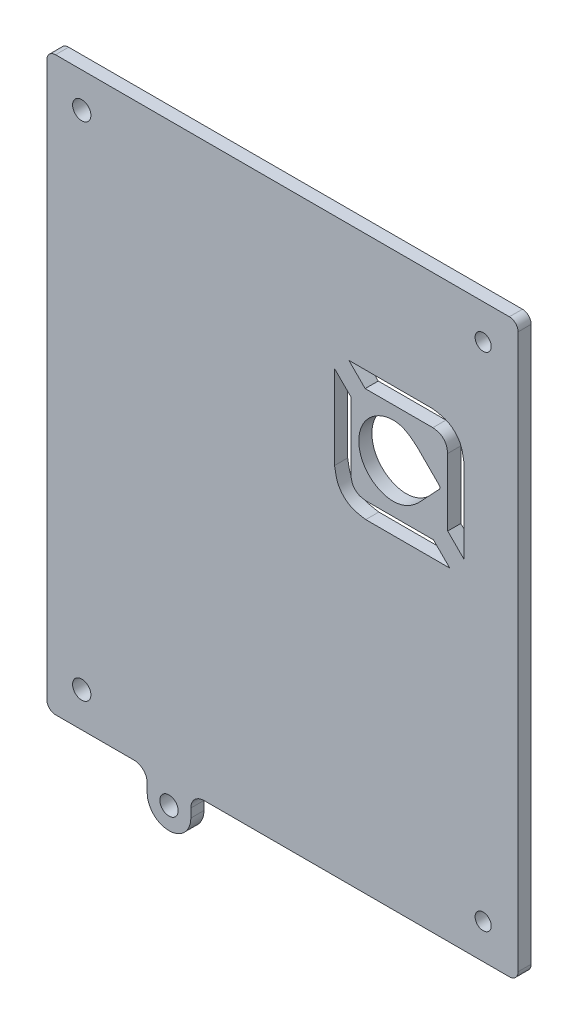
SolidWorks part; units mm, degrees
material "6061-T6 Black anodised"
ref_plane "Front Plane" through (0, 0, 0) normal (0, 0, 1) x (1, 0, 0)
ref_plane "Top Plane" through (0, 0, 0) normal (0, 1, 0) x (1, 0, 0)
ref_plane "Right Plane" through (0, 0, 0) normal (1, 0, 0) x (0, 0, -1)
sketch "Model" plane through (0, 0, 0) normal (0, 0, 1) x (1, 0, 0)
  line L0 (104.1673, 32.1811) -> (4.1672, 32.1811)
  line L1 (104.1673, 155.1806) -> (104.1673, 32.1811)
  line L2 (4.1672, 155.1806) -> (104.1673, 155.1806)
  line L3 (4.1672, 32.1811) -> (4.1672, 155.1806)
  line L4 (44.9158, 146.4259) -> (47.4224, 146.4259)
  line L5 (47.4224, 146.4259) -> (47.4224, 148.9326)
  line L6 (47.4224, 148.9326) -> (44.9158, 148.9326)
  line L7 (44.9158, 148.9326) -> (44.9158, 146.4259)
  line L8 (77.4127, 147.4278) -> (79.9193, 147.4278)
  line L9 (79.9193, 147.4278) -> (79.9193, 149.9344)
  line L10 (79.9193, 149.9344) -> (77.4127, 149.9344)
  line L11 (77.4127, 149.9344) -> (77.4127, 147.4278)
  line L12 (6.3266, 141.9721) -> (8.3592, 141.9721)
  line L13 (8.3592, 141.9721) -> (8.3592, 144.0047)
  line L14 (8.3592, 144.0047) -> (6.3266, 144.0047)
  line L15 (6.3266, 144.0047) -> (6.3266, 141.9721)
  line L16 (6.3266, 121.6529) -> (8.3592, 121.6529)
  line L17 (8.3592, 121.6529) -> (8.3592, 123.6855)
  line L18 (8.3592, 123.6855) -> (6.3266, 123.6855)
  line L19 (6.3266, 123.6855) -> (6.3266, 121.6529)
  line L20 (6.3266, 101.3324) -> (8.3592, 101.3324)
  line L21 (8.3592, 101.3324) -> (8.3592, 103.365)
  line L22 (8.3592, 103.365) -> (6.3266, 103.365)
  line L23 (6.3266, 103.365) -> (6.3266, 101.3324)
  line L24 (6.3266, 81.0118) -> (8.3592, 81.0118)
  line L25 (8.3592, 81.0118) -> (8.3592, 83.0444)
  line L26 (8.3592, 83.0444) -> (6.3266, 83.0444)
  line L27 (6.3266, 83.0444) -> (6.3266, 81.0118)
  line L28 (6.3266, 60.6927) -> (8.3592, 60.6927)
  line L29 (8.3592, 60.6927) -> (8.3592, 62.7253)
  line L30 (8.3592, 62.7253) -> (6.3266, 62.7253)
  line L31 (6.3266, 62.7253) -> (6.3266, 60.6927)
  line L32 (85.9221, 148.4144) -> (87.9547, 148.4144)
  line L33 (87.9547, 148.4144) -> (87.9547, 150.447)
  line L34 (87.9547, 150.447) -> (85.9221, 150.447)
  line L35 (85.9221, 150.447) -> (85.9221, 148.4144)
  line L36 (6.3266, 50.5324) -> (8.3592, 50.5324)
  line L37 (8.3592, 50.5324) -> (8.3592, 52.565)
  line L38 (8.3592, 52.565) -> (6.3266, 52.565)
  line L39 (6.3266, 52.565) -> (6.3266, 50.5324)
  line L40 (6.3266, 42.9118) -> (8.3592, 42.9118)
  line L41 (8.3592, 42.9118) -> (8.3592, 44.9444)
  line L42 (8.3592, 44.9444) -> (6.3266, 44.9444)
  line L43 (6.3266, 44.9444) -> (6.3266, 42.9118)
  line L44 (52.8726, 50.0418) -> (54.3815, 50.0418)
  line L45 (54.3815, 50.0418) -> (54.3815, 51.5508)
  line L46 (54.3815, 51.5508) -> (52.8726, 51.5508)
  line L47 (52.8726, 51.5508) -> (52.8726, 50.0418)
  line L48 (58.4219, 130.1637) -> (60.4545, 130.1637)
  line L49 (60.4545, 130.1637) -> (60.4545, 132.1963)
  line L50 (60.4545, 132.1963) -> (58.4219, 132.1963)
  line L51 (58.4219, 132.1963) -> (58.4219, 130.1637)
  line L52 (97.8807, 141.1439) -> (99.9133, 141.1439)
  line L53 (99.9133, 141.1439) -> (99.9133, 143.1765)
  line L54 (99.9133, 143.1765) -> (97.8807, 143.1765)
  line L55 (97.8807, 143.1765) -> (97.8807, 141.1439)
  line L56 (48.438, 37.3046) -> (48.438, 37.0552)
  line L57 (49.9456, 37.0552) -> (49.9456, 37.3046)
  line L58 (52.8877, 37.3046) -> (52.8877, 37.0552)
  line L59 (54.3967, 37.0552) -> (54.3967, 37.3046)
  line L60 (54.3126, 34.0993) -> (54.3126, 33.8995)
  line L61 (56.7201, 33.8995) -> (56.7201, 34.0993)
  line L62 (46.1133, 34.0993) -> (46.1133, 33.8995)
  line L63 (48.5207, 33.8995) -> (48.5207, 34.0993)
  line L64 (82.9607, 49.0165) -> (84.9933, 49.0165)
  line L65 (84.9933, 49.0165) -> (84.9933, 51.0492)
  line L66 (84.9933, 51.0492) -> (82.9607, 51.0492)
  line L67 (82.9607, 51.0492) -> (82.9607, 49.0165)
  line L68 (29.8828, 70.9163) -> (31.9154, 70.9163)
  line L69 (31.9154, 70.9163) -> (31.9154, 72.9489)
  line L70 (31.9154, 72.9489) -> (29.8828, 72.9489)
  line L71 (29.8828, 72.9489) -> (29.8828, 70.9163)
  line L72 (29.8828, 68.1658) -> (31.9154, 68.1658)
  line L73 (31.9154, 68.1658) -> (31.9154, 70.1984)
  line L74 (31.9154, 70.1984) -> (29.8828, 70.1984)
  line L75 (29.8828, 70.1984) -> (29.8828, 68.1658)
  line L76 (29.8828, 108.6649) -> (31.9154, 108.6649)
  line L77 (31.9154, 108.6649) -> (31.9154, 110.6975)
  line L78 (31.9154, 110.6975) -> (29.8828, 110.6975)
  line L79 (29.8828, 110.6975) -> (29.8828, 108.6649)
  line L80 (29.8828, 111.4141) -> (31.9154, 111.4141)
  line L81 (31.9154, 111.4141) -> (31.9154, 113.4467)
  line L82 (31.9154, 113.4467) -> (29.8828, 113.4467)
  line L83 (29.8828, 113.4467) -> (29.8828, 111.4141)
  line L84 (29.8828, 91.1652) -> (31.9154, 91.1652)
  line L85 (31.9154, 91.1652) -> (31.9154, 93.1978)
  line L86 (31.9154, 93.1978) -> (29.8828, 93.1978)
  line L87 (29.8828, 93.1978) -> (29.8828, 91.1652)
  line L88 (29.8828, 88.4147) -> (31.9154, 88.4147)
  line L89 (31.9154, 88.4147) -> (31.9154, 90.4473)
  line L90 (31.9154, 90.4473) -> (29.8828, 90.4473)
  line L91 (29.8828, 90.4473) -> (29.8828, 88.4147)
  line L92 (29.8828, 128.6658) -> (31.9154, 128.6658)
  line L93 (31.9154, 128.6658) -> (31.9154, 130.6984)
  line L94 (31.9154, 130.6984) -> (29.8828, 130.6984)
  line L95 (29.8828, 130.6984) -> (29.8828, 128.6658)
  line L96 (29.8828, 131.4163) -> (31.9154, 131.4163)
  line L97 (31.9154, 131.4163) -> (31.9154, 133.4489)
  line L98 (31.9154, 133.4489) -> (29.8828, 133.4489)
  line L99 (29.8828, 133.4489) -> (29.8828, 131.4163)
  line L100 (48.1611, 135.1453) -> (50.1937, 135.1453)
  line L101 (50.1937, 135.1453) -> (50.1937, 137.1779)
  line L102 (50.1937, 137.1779) -> (48.1611, 137.1779)
  line L103 (48.1611, 137.1779) -> (48.1611, 135.1453)
  line L104 (11.4074, 121.6529) -> (13.44, 121.6529)
  line L105 (13.44, 121.6529) -> (13.44, 123.6855)
  line L106 (13.44, 123.6855) -> (11.4074, 123.6855)
  line L107 (11.4074, 123.6855) -> (11.4074, 121.6529)
  line L108 (104.1673, 32.1811) -> (4.1672, 32.1811)
  line L109 (104.1673, 155.1806) -> (104.1673, 32.1811)
  line L110 (4.1672, 155.1806) -> (104.1673, 155.1806)
  line L111 (4.1672, 32.1811) -> (4.1672, 155.1806)
  spline S0 degree 3 poles (55.1711, 147.6799) (55.1711, 149.685) (52.1643, 149.685) (52.1643, 147.6799) knots 0 0 0 0 1 1 1 1
  spline S1 degree 3 poles (52.1643, 147.6799) (52.1643, 145.6749) (55.1711, 145.6749) (55.1711, 147.6799) knots 0 0 0 0 1 1 1 1
  spline S2 degree 3 poles (75.1706, 148.6804) (75.1706, 150.6854) (72.1637, 150.6854) (72.1637, 148.6804) knots 0 0 0 0 1 1 1 1
  spline S3 degree 3 poles (72.1637, 148.6804) (72.1637, 146.6754) (75.1706, 146.6754) (75.1706, 148.6804) knots 0 0 0 0 1 1 1 1
  spline S4 degree 3 poles (8.3592, 140.448) (8.3592, 141.8026) (6.3266, 141.8026) (6.3266, 140.448) knots 0 0 0 0 1 1 1 1
  spline S5 degree 3 poles (6.3266, 140.448) (6.3266, 139.0934) (8.3592, 139.0934) (8.3592, 140.448) knots 0 0 0 0 1 1 1 1
  spline S6 degree 3 poles (8.3592, 137.9083) (8.3592, 139.2629) (6.3266, 139.2629) (6.3266, 137.9083) knots 0 0 0 0 1 1 1 1
  spline S7 degree 3 poles (6.3266, 137.9083) (6.3266, 136.5537) (8.3592, 136.5537) (8.3592, 137.9083) knots 0 0 0 0 1 1 1 1
  spline S8 degree 3 poles (8.3592, 135.3686) (8.3592, 136.7232) (6.3266, 136.7232) (6.3266, 135.3686) knots 0 0 0 0 1 1 1 1
  spline S9 degree 3 poles (6.3266, 135.3686) (6.3266, 134.0139) (8.3592, 134.0139) (8.3592, 135.3686) knots 0 0 0 0 1 1 1 1
  spline S10 degree 3 poles (8.3592, 132.8288) (8.3592, 134.1834) (6.3266, 134.1834) (6.3266, 132.8288) knots 0 0 0 0 1 1 1 1
  spline S11 degree 3 poles (6.3266, 132.8288) (6.3266, 131.4742) (8.3592, 131.4742) (8.3592, 132.8288) knots 0 0 0 0 1 1 1 1
  spline S12 degree 3 poles (8.3592, 130.2891) (8.3592, 131.6437) (6.3266, 131.6437) (6.3266, 130.2891) knots 0 0 0 0 1 1 1 1
  spline S13 degree 3 poles (6.3266, 130.2891) (6.3266, 128.9331) (8.3592, 128.9331) (8.3592, 130.2891) knots 0 0 0 0 1 1 1 1
  spline S14 degree 3 poles (8.3592, 127.748) (8.3592, 129.1026) (6.3266, 129.1026) (6.3266, 127.748) knots 0 0 0 0 1 1 1 1
  spline S15 degree 3 poles (6.3266, 127.748) (6.3266, 126.3934) (8.3592, 126.3934) (8.3592, 127.748) knots 0 0 0 0 1 1 1 1
  spline S16 degree 3 poles (8.3592, 120.1288) (8.3592, 121.4834) (6.3266, 121.4834) (6.3266, 120.1288) knots 0 0 0 0 1 1 1 1
  spline S17 degree 3 poles (6.3266, 120.1288) (6.3266, 118.7742) (8.3592, 118.7742) (8.3592, 120.1288) knots 0 0 0 0 1 1 1 1
  spline S18 degree 3 poles (8.3592, 117.5891) (8.3592, 118.9437) (6.3266, 118.9437) (6.3266, 117.5891) knots 0 0 0 0 1 1 1 1
  spline S19 degree 3 poles (6.3266, 117.5891) (6.3266, 116.2331) (8.3592, 116.2331) (8.3592, 117.5891) knots 0 0 0 0 1 1 1 1
  spline S20 degree 3 poles (8.3592, 115.048) (8.3592, 116.4026) (6.3266, 116.4026) (6.3266, 115.048) knots 0 0 0 0 1 1 1 1
  spline S21 degree 3 poles (6.3266, 115.048) (6.3266, 113.6934) (8.3592, 113.6934) (8.3592, 115.048) knots 0 0 0 0 1 1 1 1
  spline S22 degree 3 poles (8.3592, 112.5083) (8.3592, 113.8629) (6.3266, 113.8629) (6.3266, 112.5083) knots 0 0 0 0 1 1 1 1
  spline S23 degree 3 poles (6.3266, 112.5083) (6.3266, 111.1537) (8.3592, 111.1537) (8.3592, 112.5083) knots 0 0 0 0 1 1 1 1
  spline S24 degree 3 poles (8.3592, 109.9686) (8.3592, 111.3232) (6.3266, 111.3232) (6.3266, 109.9686) knots 0 0 0 0 1 1 1 1
  spline S25 degree 3 poles (6.3266, 109.9686) (6.3266, 108.6139) (8.3592, 108.6139) (8.3592, 109.9686) knots 0 0 0 0 1 1 1 1
  spline S26 degree 3 poles (8.3592, 107.4288) (8.3592, 108.7834) (6.3266, 108.7834) (6.3266, 107.4288) knots 0 0 0 0 1 1 1 1
  spline S27 degree 3 poles (6.3266, 107.4288) (6.3266, 106.0742) (8.3592, 106.0742) (8.3592, 107.4288) knots 0 0 0 0 1 1 1 1
  spline S28 degree 3 poles (8.3592, 99.8083) (8.3592, 101.1629) (6.3266, 101.1629) (6.3266, 99.8083) knots 0 0 0 0 1 1 1 1
  spline S29 degree 3 poles (6.3266, 99.8083) (6.3266, 98.4537) (8.3592, 98.4537) (8.3592, 99.8083) knots 0 0 0 0 1 1 1 1
  spline S30 degree 3 poles (8.3592, 97.2686) (8.3592, 98.6232) (6.3266, 98.6232) (6.3266, 97.2686) knots 0 0 0 0 1 1 1 1
  spline S31 degree 3 poles (6.3266, 97.2686) (6.3266, 95.9139) (8.3592, 95.9139) (8.3592, 97.2686) knots 0 0 0 0 1 1 1 1
  spline S32 degree 3 poles (8.3592, 94.7288) (8.3592, 96.0834) (6.3266, 96.0834) (6.3266, 94.7288) knots 0 0 0 0 1 1 1 1
  spline S33 degree 3 poles (6.3266, 94.7288) (6.3266, 93.3742) (8.3592, 93.3742) (8.3592, 94.7288) knots 0 0 0 0 1 1 1 1
  spline S34 degree 3 poles (8.3592, 92.1891) (8.3592, 93.5437) (6.3266, 93.5437) (6.3266, 92.1891) knots 0 0 0 0 1 1 1 1
  spline S35 degree 3 poles (6.3266, 92.1891) (6.3266, 90.8331) (8.3592, 90.8331) (8.3592, 92.1891) knots 0 0 0 0 1 1 1 1
  spline S36 degree 3 poles (8.3592, 89.648) (8.3592, 91.0026) (6.3266, 91.0026) (6.3266, 89.648) knots 0 0 0 0 1 1 1 1
  spline S37 degree 3 poles (6.3266, 89.648) (6.3266, 88.2934) (8.3592, 88.2934) (8.3592, 89.648) knots 0 0 0 0 1 1 1 1
  spline S38 degree 3 poles (8.3592, 87.1083) (8.3592, 88.4629) (6.3266, 88.4629) (6.3266, 87.1083) knots 0 0 0 0 1 1 1 1
  spline S39 degree 3 poles (6.3266, 87.1083) (6.3266, 85.7537) (8.3592, 85.7537) (8.3592, 87.1083) knots 0 0 0 0 1 1 1 1
  spline S40 degree 3 poles (8.3592, 79.4891) (8.3592, 80.8437) (6.3266, 80.8437) (6.3266, 79.4891) knots 0 0 0 0 1 1 1 1
  spline S41 degree 3 poles (6.3266, 79.4891) (6.3266, 78.1331) (8.3592, 78.1331) (8.3592, 79.4891) knots 0 0 0 0 1 1 1 1
  spline S42 degree 3 poles (8.3592, 76.948) (8.3592, 78.3026) (6.3266, 78.3026) (6.3266, 76.948) knots 0 0 0 0 1 1 1 1
  spline S43 degree 3 poles (6.3266, 76.948) (6.3266, 75.5934) (8.3592, 75.5934) (8.3592, 76.948) knots 0 0 0 0 1 1 1 1
  spline S44 degree 3 poles (8.3592, 74.4083) (8.3592, 75.7629) (6.3266, 75.7629) (6.3266, 74.4083) knots 0 0 0 0 1 1 1 1
  spline S45 degree 3 poles (6.3266, 74.4083) (6.3266, 73.0537) (8.3592, 73.0537) (8.3592, 74.4083) knots 0 0 0 0 1 1 1 1
  spline S46 degree 3 poles (8.3592, 71.8685) (8.3592, 73.2232) (6.3266, 73.2232) (6.3266, 71.8685) knots 0 0 0 0 1 1 1 1
  spline S47 degree 3 poles (6.3266, 71.8685) (6.3266, 70.5139) (8.3592, 70.5139) (8.3592, 71.8685) knots 0 0 0 0 1 1 1 1
  spline S48 degree 3 poles (8.3592, 69.3288) (8.3592, 70.6834) (6.3266, 70.6834) (6.3266, 69.3288) knots 0 0 0 0 1 1 1 1
  spline S49 degree 3 poles (6.3266, 69.3288) (6.3266, 67.9742) (8.3592, 67.9742) (8.3592, 69.3288) knots 0 0 0 0 1 1 1 1
  spline S50 degree 3 poles (8.3592, 66.7891) (8.3592, 68.1437) (6.3266, 68.1437) (6.3266, 66.7891) knots 0 0 0 0 1 1 1 1
  spline S51 degree 3 poles (6.3266, 66.7891) (6.3266, 65.4331) (8.3592, 65.4331) (8.3592, 66.7891) knots 0 0 0 0 1 1 1 1
  spline S52 degree 3 poles (8.3592, 59.1686) (8.3592, 60.5232) (6.3266, 60.5232) (6.3266, 59.1686) knots 0 0 0 0 1 1 1 1
  spline S53 degree 3 poles (6.3266, 59.1686) (6.3266, 57.8139) (8.3592, 57.8139) (8.3592, 59.1686) knots 0 0 0 0 1 1 1 1
  spline S54 degree 3 poles (8.3592, 56.6288) (8.3592, 57.9834) (6.3266, 57.9834) (6.3266, 56.6288) knots 0 0 0 0 1 1 1 1
  spline S55 degree 3 poles (6.3266, 56.6288) (6.3266, 55.2742) (8.3592, 55.2742) (8.3592, 56.6288) knots 0 0 0 0 1 1 1 1
  spline S56 degree 3 poles (8.3592, 54.0891) (8.3592, 55.4437) (6.3266, 55.4437) (6.3266, 54.0891) knots 0 0 0 0 1 1 1 1
  spline S57 degree 3 poles (6.3266, 54.0891) (6.3266, 52.7331) (8.3592, 52.7331) (8.3592, 54.0891) knots 0 0 0 0 1 1 1 1
  spline S58 degree 3 poles (85.4149, 149.4301) (85.4149, 150.7847) (83.3823, 150.7847) (83.3823, 149.4301) knots 0 0 0 0 1 1 1 1
  spline S59 degree 3 poles (83.3823, 149.4301) (83.3823, 148.0754) (85.4149, 148.0754) (85.4149, 149.4301) knots 0 0 0 0 1 1 1 1
  spline S60 degree 3 poles (8.3592, 49.0083) (8.3592, 50.3629) (6.3266, 50.3629) (6.3266, 49.0083) knots 0 0 0 0 1 1 1 1
  spline S61 degree 3 poles (6.3266, 49.0083) (6.3266, 47.6537) (8.3592, 47.6537) (8.3592, 49.0083) knots 0 0 0 0 1 1 1 1
  spline S62 degree 3 poles (8.3592, 41.3891) (8.3592, 42.7437) (6.3266, 42.7437) (6.3266, 41.3891) knots 0 0 0 0 1 1 1 1
  spline S63 degree 3 poles (6.3266, 41.3891) (6.3266, 40.0331) (8.3592, 40.0331) (8.3592, 41.3891) knots 0 0 0 0 1 1 1 1
  spline S64 degree 3 poles (54.3815, 52.0661) (54.3815, 53.0721) (52.8726, 53.0721) (52.8726, 52.0661) knots 0 0 0 0 1 1 1 1
  spline S65 degree 3 poles (52.8726, 52.0661) (52.8726, 51.0602) (54.3815, 51.0602) (54.3815, 52.0661) knots 0 0 0 0 1 1 1 1
  spline S66 degree 3 poles (55.6507, 50.797) (55.6507, 51.8029) (54.1417, 51.8029) (54.1417, 50.797) knots 0 0 0 0 1 1 1 1
  spline S67 degree 3 poles (54.1417, 50.797) (54.1417, 49.791) (55.6507, 49.791) (55.6507, 50.797) knots 0 0 0 0 1 1 1 1
  spline S68 degree 3 poles (55.6507, 52.0661) (55.6507, 53.0721) (54.1417, 53.0721) (54.1417, 52.0661) knots 0 0 0 0 1 1 1 1
  spline S69 degree 3 poles (54.1417, 52.0661) (54.1417, 51.0602) (55.6507, 51.0602) (55.6507, 52.0661) knots 0 0 0 0 1 1 1 1
  spline S70 degree 3 poles (56.9212, 50.797) (56.9212, 51.8029) (55.4123, 51.8029) (55.4123, 50.797) knots 0 0 0 0 1 1 1 1
  spline S71 degree 3 poles (55.4123, 50.797) (55.4123, 49.791) (56.9212, 49.791) (56.9212, 50.797) knots 0 0 0 0 1 1 1 1
  spline S72 degree 3 poles (56.9212, 52.0661) (56.9212, 53.0721) (55.4123, 53.0721) (55.4123, 52.0661) knots 0 0 0 0 1 1 1 1
  spline S73 degree 3 poles (55.4123, 52.0661) (55.4123, 51.0602) (56.9212, 51.0602) (56.9212, 52.0661) knots 0 0 0 0 1 1 1 1
  spline S74 degree 3 poles (58.1904, 50.797) (58.1904, 51.8029) (56.6828, 51.8029) (56.6828, 50.797) knots 0 0 0 0 1 1 1 1
  spline S75 degree 3 poles (56.6828, 50.797) (56.6828, 49.791) (58.1904, 49.791) (58.1904, 50.797) knots 0 0 0 0 1 1 1 1
  spline S76 degree 3 poles (58.1904, 52.0661) (58.1904, 53.0721) (56.6828, 53.0721) (56.6828, 52.0661) knots 0 0 0 0 1 1 1 1
  spline S77 degree 3 poles (56.6828, 52.0661) (56.6828, 51.0602) (58.1904, 51.0602) (58.1904, 52.0661) knots 0 0 0 0 1 1 1 1
  spline S78 degree 3 poles (59.461, 50.797) (59.461, 51.8029) (57.952, 51.8029) (57.952, 50.797) knots 0 0 0 0 1 1 1 1
  spline S79 degree 3 poles (57.952, 50.797) (57.952, 49.791) (59.461, 49.791) (59.461, 50.797) knots 0 0 0 0 1 1 1 1
  spline S80 degree 3 poles (59.461, 52.0661) (59.461, 53.0721) (57.952, 53.0721) (57.952, 52.0661) knots 0 0 0 0 1 1 1 1
  spline S81 degree 3 poles (57.952, 52.0661) (57.952, 51.0602) (59.461, 51.0602) (59.461, 52.0661) knots 0 0 0 0 1 1 1 1
  spline S82 degree 3 poles (57.9148, 131.1793) (57.9148, 132.5353) (55.8822, 132.5353) (55.8822, 131.1793) knots 0 0 0 0 1 1 1 1
  spline S83 degree 3 poles (55.8822, 131.1793) (55.8822, 129.8247) (57.9148, 129.8247) (57.9148, 131.1793) knots 0 0 0 0 1 1 1 1
  spline S84 degree 3 poles (63.2437, 36.9311) (63.2437, 37.9371) (61.7347, 37.9371) (61.7347, 36.9311) knots 0 0 0 0 1 1 1 1
  spline S85 degree 3 poles (61.7347, 36.9311) (61.7347, 35.9252) (63.2437, 35.9252) (63.2437, 36.9311) knots 0 0 0 0 1 1 1 1
  spline S86 degree 3 poles (71.2239, 36.9311) (71.2239, 37.9371) (69.715, 37.9371) (69.715, 36.9311) knots 0 0 0 0 1 1 1 1
  spline S87 degree 3 poles (69.715, 36.9311) (69.715, 35.9252) (71.2239, 35.9252) (71.2239, 36.9311) knots 0 0 0 0 1 1 1 1
  spline S88 degree 3 poles (102.453, 142.1609) (102.453, 143.5155) (100.4204, 143.5155) (100.4204, 142.1609) knots 0 0 0 0 1 1 1 1
  spline S89 degree 3 poles (100.4204, 142.1609) (100.4204, 140.8063) (102.453, 140.8063) (102.453, 142.1609) knots 0 0 0 0 1 1 1 1
  spline S90 degree 3 poles (99.9133, 129.4609) (99.9133, 130.8155) (97.8807, 130.8155) (97.8807, 129.4609) knots 0 0 0 0 1 1 1 1
  spline S91 degree 3 poles (97.8807, 129.4609) (97.8807, 128.1063) (99.9133, 128.1063) (99.9133, 129.4609) knots 0 0 0 0 1 1 1 1
  spline S92 degree 3 poles (102.453, 139.6198) (102.453, 140.9744) (100.4204, 140.9744) (100.4204, 139.6198) knots 0 0 0 0 1 1 1 1
  spline S93 degree 3 poles (100.4204, 139.6198) (100.4204, 138.2652) (102.453, 138.2652) (102.453, 139.6198) knots 0 0 0 0 1 1 1 1
  spline S94 degree 3 poles (99.9133, 126.9198) (99.9133, 128.2744) (97.8807, 128.2744) (97.8807, 126.9198) knots 0 0 0 0 1 1 1 1
  spline S95 degree 3 poles (97.8807, 126.9198) (97.8807, 125.5652) (99.9133, 125.5652) (99.9133, 126.9198) knots 0 0 0 0 1 1 1 1
  spline S96 degree 3 poles (102.453, 137.0801) (102.453, 138.4347) (100.4204, 138.4347) (100.4204, 137.0801) knots 0 0 0 0 1 1 1 1
  spline S97 degree 3 poles (100.4204, 137.0801) (100.4204, 135.7255) (102.453, 135.7255) (102.453, 137.0801) knots 0 0 0 0 1 1 1 1
  spline S98 degree 3 poles (99.9133, 124.3801) (99.9133, 125.7347) (97.8807, 125.7347) (97.8807, 124.3801) knots 0 0 0 0 1 1 1 1
  spline S99 degree 3 poles (97.8807, 124.3801) (97.8807, 123.0255) (99.9133, 123.0255) (99.9133, 124.3801) knots 0 0 0 0 1 1 1 1
  spline S100 degree 3 poles (102.453, 134.5403) (102.453, 135.895) (100.4204, 135.895) (100.4204, 134.5403) knots 0 0 0 0 1 1 1 1
  spline S101 degree 3 poles (100.4204, 134.5403) (100.4204, 133.1857) (102.453, 133.1857) (102.453, 134.5403) knots 0 0 0 0 1 1 1 1
  spline S102 degree 3 poles (99.9133, 121.8404) (99.9133, 123.195) (97.8807, 123.195) (97.8807, 121.8404) knots 0 0 0 0 1 1 1 1
  spline S103 degree 3 poles (97.8807, 121.8404) (97.8807, 120.4857) (99.9133, 120.4857) (99.9133, 121.8404) knots 0 0 0 0 1 1 1 1
  spline S104 degree 3 poles (102.453, 132.0006) (102.453, 133.3552) (100.4204, 133.3552) (100.4204, 132.0006) knots 0 0 0 0 1 1 1 1
  spline S105 degree 3 poles (100.4204, 132.0006) (100.4204, 130.646) (102.453, 130.646) (102.453, 132.0006) knots 0 0 0 0 1 1 1 1
  spline S106 degree 3 poles (99.9133, 119.3006) (99.9133, 120.6552) (97.8807, 120.6552) (97.8807, 119.3006) knots 0 0 0 0 1 1 1 1
  spline S107 degree 3 poles (97.8807, 119.3006) (97.8807, 117.946) (99.9133, 117.946) (99.9133, 119.3006) knots 0 0 0 0 1 1 1 1
  spline S108 degree 3 poles (102.453, 129.4609) (102.453, 130.8155) (100.4204, 130.8155) (100.4204, 129.4609) knots 0 0 0 0 1 1 1 1
  spline S109 degree 3 poles (100.4204, 129.4609) (100.4204, 128.1063) (102.453, 128.1063) (102.453, 129.4609) knots 0 0 0 0 1 1 1 1
  spline S110 degree 3 poles (99.9133, 116.7609) (99.9133, 118.1155) (97.8807, 118.1155) (97.8807, 116.7609) knots 0 0 0 0 1 1 1 1
  spline S111 degree 3 poles (97.8807, 116.7609) (97.8807, 115.4063) (99.9133, 115.4063) (99.9133, 116.7609) knots 0 0 0 0 1 1 1 1
  spline S112 degree 3 poles (102.453, 126.9198) (102.453, 128.2744) (100.4204, 128.2744) (100.4204, 126.9198) knots 0 0 0 0 1 1 1 1
  spline S113 degree 3 poles (100.4204, 126.9198) (100.4204, 125.5652) (102.453, 125.5652) (102.453, 126.9198) knots 0 0 0 0 1 1 1 1
  spline S114 degree 3 poles (99.9133, 114.2198) (99.9133, 115.5744) (97.8807, 115.5744) (97.8807, 114.2198) knots 0 0 0 0 1 1 1 1
  spline S115 degree 3 poles (97.8807, 114.2198) (97.8807, 112.8652) (99.9133, 112.8652) (99.9133, 114.2198) knots 0 0 0 0 1 1 1 1
  spline S116 degree 3 poles (102.453, 124.3801) (102.453, 125.7347) (100.4204, 125.7347) (100.4204, 124.3801) knots 0 0 0 0 1 1 1 1
  spline S117 degree 3 poles (100.4204, 124.3801) (100.4204, 123.0255) (102.453, 123.0255) (102.453, 124.3801) knots 0 0 0 0 1 1 1 1
  spline S118 degree 3 poles (99.9133, 111.6801) (99.9133, 113.0347) (97.8807, 113.0347) (97.8807, 111.6801) knots 0 0 0 0 1 1 1 1
  spline S119 degree 3 poles (97.8807, 111.6801) (97.8807, 110.3255) (99.9133, 110.3255) (99.9133, 111.6801) knots 0 0 0 0 1 1 1 1
  spline S120 degree 3 poles (102.453, 121.8404) (102.453, 123.195) (100.4204, 123.195) (100.4204, 121.8404) knots 0 0 0 0 1 1 1 1
  spline S121 degree 3 poles (100.4204, 121.8404) (100.4204, 120.4857) (102.453, 120.4857) (102.453, 121.8404) knots 0 0 0 0 1 1 1 1
  spline S122 degree 3 poles (99.9133, 109.1404) (99.9133, 110.495) (97.8807, 110.495) (97.8807, 109.1404) knots 0 0 0 0 1 1 1 1
  spline S123 degree 3 poles (97.8807, 109.1404) (97.8807, 107.7857) (99.9133, 107.7857) (99.9133, 109.1404) knots 0 0 0 0 1 1 1 1
  spline S124 degree 3 poles (102.453, 119.3006) (102.453, 120.6552) (100.4204, 120.6552) (100.4204, 119.3006) knots 0 0 0 0 1 1 1 1
  spline S125 degree 3 poles (100.4204, 119.3006) (100.4204, 117.946) (102.453, 117.946) (102.453, 119.3006) knots 0 0 0 0 1 1 1 1
  spline S126 degree 3 poles (99.9133, 106.6006) (99.9133, 107.9552) (97.8807, 107.9552) (97.8807, 106.6006) knots 0 0 0 0 1 1 1 1
  spline S127 degree 3 poles (97.8807, 106.6006) (97.8807, 105.246) (99.9133, 105.246) (99.9133, 106.6006) knots 0 0 0 0 1 1 1 1
  spline S128 degree 3 poles (102.453, 116.7609) (102.453, 118.1155) (100.4204, 118.1155) (100.4204, 116.7609) knots 0 0 0 0 1 1 1 1
  spline S129 degree 3 poles (100.4204, 116.7609) (100.4204, 115.4063) (102.453, 115.4063) (102.453, 116.7609) knots 0 0 0 0 1 1 1 1
  spline S130 degree 3 poles (99.9133, 104.0609) (99.9133, 105.4155) (97.8807, 105.4155) (97.8807, 104.0609) knots 0 0 0 0 1 1 1 1
  spline S131 degree 3 poles (97.8807, 104.0609) (97.8807, 102.7063) (99.9133, 102.7063) (99.9133, 104.0609) knots 0 0 0 0 1 1 1 1
  spline S132 degree 3 poles (102.453, 114.2198) (102.453, 115.5744) (100.4204, 115.5744) (100.4204, 114.2198) knots 0 0 0 0 1 1 1 1
  spline S133 degree 3 poles (100.4204, 114.2198) (100.4204, 112.8652) (102.453, 112.8652) (102.453, 114.2198) knots 0 0 0 0 1 1 1 1
  spline S134 degree 3 poles (102.453, 111.6801) (102.453, 113.0347) (100.4204, 113.0347) (100.4204, 111.6801) knots 0 0 0 0 1 1 1 1
  spline S135 degree 3 poles (100.4204, 111.6801) (100.4204, 110.3255) (102.453, 110.3255) (102.453, 111.6801) knots 0 0 0 0 1 1 1 1
  spline S136 degree 3 poles (99.9133, 101.5198) (99.9133, 102.8744) (97.8807, 102.8744) (97.8807, 101.5198) knots 0 0 0 0 1 1 1 1
  spline S137 degree 3 poles (97.8807, 101.5198) (97.8807, 100.1652) (99.9133, 100.1652) (99.9133, 101.5198) knots 0 0 0 0 1 1 1 1
  spline S138 degree 3 poles (102.453, 109.1404) (102.453, 110.495) (100.4204, 110.495) (100.4204, 109.1404) knots 0 0 0 0 1 1 1 1
  spline S139 degree 3 poles (100.4204, 109.1404) (100.4204, 107.7857) (102.453, 107.7857) (102.453, 109.1404) knots 0 0 0 0 1 1 1 1
  spline S140 degree 3 poles (102.453, 104.0609) (102.453, 105.4155) (100.4204, 105.4155) (100.4204, 104.0609) knots 0 0 0 0 1 1 1 1
  spline S141 degree 3 poles (100.4204, 104.0609) (100.4204, 102.7063) (102.453, 102.7063) (102.453, 104.0609) knots 0 0 0 0 1 1 1 1
  spline S142 degree 3 poles (102.453, 101.5198) (102.453, 102.8744) (100.4204, 102.8744) (100.4204, 101.5198) knots 0 0 0 0 1 1 1 1
  spline S143 degree 3 poles (100.4204, 101.5198) (100.4204, 100.1652) (102.453, 100.1652) (102.453, 101.5198) knots 0 0 0 0 1 1 1 1
  spline S144 degree 3 poles (102.453, 98.9801) (102.453, 100.3347) (100.4204, 100.3347) (100.4204, 98.9801) knots 0 0 0 0 1 1 1 1
  spline S145 degree 3 poles (100.4204, 98.9801) (100.4204, 97.6255) (102.453, 97.6255) (102.453, 98.9801) knots 0 0 0 0 1 1 1 1
  spline S146 degree 3 poles (102.453, 96.4404) (102.453, 97.795) (100.4204, 97.795) (100.4204, 96.4404) knots 0 0 0 0 1 1 1 1
  spline S147 degree 3 poles (100.4204, 96.4404) (100.4204, 95.0857) (102.453, 95.0857) (102.453, 96.4404) knots 0 0 0 0 1 1 1 1
  spline S148 degree 3 poles (99.9133, 98.9801) (99.9133, 100.3347) (97.8807, 100.3347) (97.8807, 98.9801) knots 0 0 0 0 1 1 1 1
  spline S149 degree 3 poles (97.8807, 98.9801) (97.8807, 97.6255) (99.9133, 97.6255) (99.9133, 98.9801) knots 0 0 0 0 1 1 1 1
  spline S150 degree 3 poles (99.9133, 96.4404) (99.9133, 97.795) (97.8807, 97.795) (97.8807, 96.4404) knots 0 0 0 0 1 1 1 1
  spline S151 degree 3 poles (97.8807, 96.4404) (97.8807, 95.0857) (99.9133, 95.0857) (99.9133, 96.4404) knots 0 0 0 0 1 1 1 1
  spline S152 degree 3 poles (99.9133, 139.6198) (99.9133, 140.9744) (97.8807, 140.9744) (97.8807, 139.6198) knots 0 0 0 0 1 1 1 1
  spline S153 degree 3 poles (97.8807, 139.6198) (97.8807, 138.2652) (99.9133, 138.2652) (99.9133, 139.6198) knots 0 0 0 0 1 1 1 1
  spline S154 degree 3 poles (99.9133, 137.0801) (99.9133, 138.4347) (97.8807, 138.4347) (97.8807, 137.0801) knots 0 0 0 0 1 1 1 1
  spline S155 degree 3 poles (97.8807, 137.0801) (97.8807, 135.7255) (99.9133, 135.7255) (99.9133, 137.0801) knots 0 0 0 0 1 1 1 1
  spline S156 degree 3 poles (99.9133, 134.5403) (99.9133, 135.895) (97.8807, 135.895) (97.8807, 134.5403) knots 0 0 0 0 1 1 1 1
  spline S157 degree 3 poles (97.8807, 134.5403) (97.8807, 133.1857) (99.9133, 133.1857) (99.9133, 134.5403) knots 0 0 0 0 1 1 1 1
  spline S158 degree 3 poles (99.9133, 132.0006) (99.9133, 133.3552) (97.8807, 133.3552) (97.8807, 132.0006) knots 0 0 0 0 1 1 1 1
  spline S159 degree 3 poles (97.8807, 132.0006) (97.8807, 130.646) (99.9133, 130.646) (99.9133, 132.0006) knots 0 0 0 0 1 1 1 1
  spline S160 degree 3 poles (99.9133, 93.9006) (99.9133, 95.2552) (97.8807, 95.2552) (97.8807, 93.9006) knots 0 0 0 0 1 1 1 1
  spline S161 degree 3 poles (97.8807, 93.9006) (97.8807, 92.546) (99.9133, 92.546) (99.9133, 93.9006) knots 0 0 0 0 1 1 1 1
  spline S162 degree 3 poles (102.453, 93.9006) (102.453, 95.2552) (100.4204, 95.2552) (100.4204, 93.9006) knots 0 0 0 0 1 1 1 1
  spline S163 degree 3 poles (100.4204, 93.9006) (100.4204, 92.546) (102.453, 92.546) (102.453, 93.9006) knots 0 0 0 0 1 1 1 1
  spline S164 degree 3 poles (102.453, 106.6006) (102.453, 107.9552) (100.4204, 107.9552) (100.4204, 106.6006) knots 0 0 0 0 1 1 1 1
  spline S165 degree 3 poles (100.4204, 106.6006) (100.4204, 105.246) (102.453, 105.246) (102.453, 106.6006) knots 0 0 0 0 1 1 1 1
  spline S166 degree 3 poles (99.9133, 91.3609) (99.9133, 92.7155) (97.8807, 92.7155) (97.8807, 91.3609) knots 0 0 0 0 1 1 1 1
  spline S167 degree 3 poles (97.8807, 91.3609) (97.8807, 90.0063) (99.9133, 90.0063) (99.9133, 91.3609) knots 0 0 0 0 1 1 1 1
  spline S168 degree 3 poles (102.453, 91.3609) (102.453, 92.7155) (100.4204, 92.7155) (100.4204, 91.3609) knots 0 0 0 0 1 1 1 1
  spline S169 degree 3 poles (100.4204, 91.3609) (100.4204, 90.0063) (102.453, 90.0063) (102.453, 91.3609) knots 0 0 0 0 1 1 1 1
  spline S170 degree 3 poles (99.9133, 88.8198) (99.9133, 90.1744) (97.8807, 90.1744) (97.8807, 88.8198) knots 0 0 0 0 1 1 1 1
  spline S171 degree 3 poles (97.8807, 88.8198) (97.8807, 87.4652) (99.9133, 87.4652) (99.9133, 88.8198) knots 0 0 0 0 1 1 1 1
  spline S172 degree 3 poles (102.453, 88.8198) (102.453, 90.1744) (100.4204, 90.1744) (100.4204, 88.8198) knots 0 0 0 0 1 1 1 1
  spline S173 degree 3 poles (100.4204, 88.8198) (100.4204, 87.4652) (102.453, 87.4652) (102.453, 88.8198) knots 0 0 0 0 1 1 1 1
  spline S174 degree 3 poles (99.9133, 86.2801) (99.9133, 87.6347) (97.8807, 87.6347) (97.8807, 86.2801) knots 0 0 0 0 1 1 1 1
  spline S175 degree 3 poles (97.8807, 86.2801) (97.8807, 84.9255) (99.9133, 84.9255) (99.9133, 86.2801) knots 0 0 0 0 1 1 1 1
  spline S176 degree 3 poles (102.453, 86.2801) (102.453, 87.6347) (100.4204, 87.6347) (100.4204, 86.2801) knots 0 0 0 0 1 1 1 1
  spline S177 degree 3 poles (100.4204, 86.2801) (100.4204, 84.9255) (102.453, 84.9255) (102.453, 86.2801) knots 0 0 0 0 1 1 1 1
  spline S178 degree 3 poles (99.9133, 83.7404) (99.9133, 85.095) (97.8807, 85.095) (97.8807, 83.7404) knots 0 0 0 0 1 1 1 1
  spline S179 degree 3 poles (97.8807, 83.7404) (97.8807, 82.3857) (99.9133, 82.3857) (99.9133, 83.7404) knots 0 0 0 0 1 1 1 1
  spline S180 degree 3 poles (102.453, 83.7404) (102.453, 85.095) (100.4204, 85.095) (100.4204, 83.7404) knots 0 0 0 0 1 1 1 1
  spline S181 degree 3 poles (100.4204, 83.7404) (100.4204, 82.3857) (102.453, 82.3857) (102.453, 83.7404) knots 0 0 0 0 1 1 1 1
  spline S182 degree 3 poles (99.9133, 81.2006) (99.9133, 82.5552) (97.8807, 82.5552) (97.8807, 81.2006) knots 0 0 0 0 1 1 1 1
  spline S183 degree 3 poles (97.8807, 81.2006) (97.8807, 79.846) (99.9133, 79.846) (99.9133, 81.2006) knots 0 0 0 0 1 1 1 1
  spline S184 degree 3 poles (102.453, 81.2006) (102.453, 82.5552) (100.4204, 82.5552) (100.4204, 81.2006) knots 0 0 0 0 1 1 1 1
  spline S185 degree 3 poles (100.4204, 81.2006) (100.4204, 79.846) (102.453, 79.846) (102.453, 81.2006) knots 0 0 0 0 1 1 1 1
  spline S186 degree 3 poles (49.9456, 37.3046) (49.9456, 38.3106) (48.438, 38.3106) (48.438, 37.3046) knots 0 0 0 0 1 1 1 1
  spline S187 degree 3 poles (48.438, 37.0552) (48.438, 36.0492) (49.9456, 36.0492) (49.9456, 37.0552) knots 0 0 0 0 1 1 1 1
  spline S188 degree 3 poles (54.3967, 37.3046) (54.3967, 38.3106) (52.8877, 38.3106) (52.8877, 37.3046) knots 0 0 0 0 1 1 1 1
  spline S189 degree 3 poles (52.8877, 37.0552) (52.8877, 36.0492) (54.3967, 36.0492) (54.3967, 37.0552) knots 0 0 0 0 1 1 1 1
  spline S190 degree 3 poles (56.7201, 34.0993) (56.7201, 35.7047) (54.3126, 35.7047) (54.3126, 34.0993) knots 0 0 0 0 1 1 1 1
  spline S191 degree 3 poles (54.3126, 33.8995) (54.3126, 32.2941) (56.7201, 32.2941) (56.7201, 33.8995) knots 0 0 0 0 1 1 1 1
  spline S192 degree 3 poles (48.5207, 34.0993) (48.5207, 35.7047) (46.1133, 35.7047) (46.1133, 34.0993) knots 0 0 0 0 1 1 1 1
  spline S193 degree 3 poles (46.1133, 33.8995) (46.1133, 32.2941) (48.5207, 32.2941) (48.5207, 33.8995) knots 0 0 0 0 1 1 1 1
  spline S194 degree 3 poles (54.4711, 34.0001) (54.4711, 34.9054) (53.1123, 34.9054) (53.1123, 34.0001) knots 0 0 0 0 1 1 1 1
  spline S195 degree 3 poles (53.1123, 34.0001) (53.1123, 33.0933) (54.4711, 33.0933) (54.4711, 34.0001) knots 0 0 0 0 1 1 1 1
  spline S196 degree 3 poles (49.721, 34.0001) (49.721, 34.9054) (48.3623, 34.9054) (48.3623, 34.0001) knots 0 0 0 0 1 1 1 1
  spline S197 degree 3 poles (48.3623, 34.0001) (48.3623, 33.0933) (49.721, 33.0933) (49.721, 34.0001) knots 0 0 0 0 1 1 1 1
  spline S198 degree 3 poles (84.606, 43.6822) (84.606, 46.2205) (80.7985, 46.2205) (80.7985, 43.6822) knots 0 0 0 0 1 1 1 1
  spline S199 degree 3 poles (80.7985, 43.6822) (80.7985, 41.1438) (84.606, 41.1438) (84.606, 43.6822) knots 0 0 0 0 1 1 1 1
  spline S200 degree 3 poles (96.0355, 43.6822) (96.0355, 46.2205) (92.228, 46.2205) (92.228, 43.6822) knots 0 0 0 0 1 1 1 1
  spline S201 degree 3 poles (92.228, 43.6822) (92.228, 41.1438) (96.0355, 41.1438) (96.0355, 43.6822) knots 0 0 0 0 1 1 1 1
  spline S202 degree 3 poles (93.8775, 52.5719) (93.8775, 53.9265) (91.8462, 53.9265) (91.8462, 52.5719) knots 0 0 0 0 1 1 1 1
  spline S203 degree 3 poles (91.8462, 52.5719) (91.8462, 51.2173) (93.8775, 51.2173) (93.8775, 52.5719) knots 0 0 0 0 1 1 1 1
  spline S204 degree 3 poles (92.6124, 50.0322) (92.6124, 51.3868) (90.5812, 51.3868) (90.5812, 50.0322) knots 0 0 0 0 1 1 1 1
  spline S205 degree 3 poles (90.5812, 50.0322) (90.5812, 48.6775) (92.6124, 48.6775) (92.6124, 50.0322) knots 0 0 0 0 1 1 1 1
  spline S206 degree 3 poles (91.3377, 52.5719) (91.3377, 53.9265) (89.3065, 53.9265) (89.3065, 52.5719) knots 0 0 0 0 1 1 1 1
  spline S207 degree 3 poles (89.3065, 52.5719) (89.3065, 51.2173) (91.3377, 51.2173) (91.3377, 52.5719) knots 0 0 0 0 1 1 1 1
  spline S208 degree 3 poles (90.0727, 50.0322) (90.0727, 51.3868) (88.0415, 51.3868) (88.0415, 50.0322) knots 0 0 0 0 1 1 1 1
  spline S209 degree 3 poles (88.0415, 50.0322) (88.0415, 48.6775) (90.0727, 48.6775) (90.0727, 50.0322) knots 0 0 0 0 1 1 1 1
  spline S210 degree 3 poles (88.798, 52.5719) (88.798, 53.9265) (86.7654, 53.9265) (86.7654, 52.5719) knots 0 0 0 0 1 1 1 1
  spline S211 degree 3 poles (86.7654, 52.5719) (86.7654, 51.2173) (88.798, 51.2173) (88.798, 52.5719) knots 0 0 0 0 1 1 1 1
  spline S212 degree 3 poles (87.533, 50.0322) (87.533, 51.3868) (85.5018, 51.3868) (85.5018, 50.0322) knots 0 0 0 0 1 1 1 1
  spline S213 degree 3 poles (85.5018, 50.0322) (85.5018, 48.6775) (87.533, 48.6775) (87.533, 50.0322) knots 0 0 0 0 1 1 1 1
  spline S214 degree 3 poles (86.2583, 52.5719) (86.2583, 53.9265) (84.2257, 53.9265) (84.2257, 52.5719) knots 0 0 0 0 1 1 1 1
  spline S215 degree 3 poles (84.2257, 52.5719) (84.2257, 51.2173) (86.2583, 51.2173) (86.2583, 52.5719) knots 0 0 0 0 1 1 1 1
  spline S216 degree 3 poles (82.1945, 46.7331) (82.1945, 48.7644) (79.1462, 48.7644) (79.1462, 46.7331) knots 0 0 0 0 1 1 1 1
  spline S217 degree 3 poles (79.1462, 46.7331) (79.1462, 44.7005) (82.1945, 44.7005) (82.1945, 46.7331) knots 0 0 0 0 1 1 1 1
  spline S218 degree 3 poles (97.6877, 46.7304) (97.6877, 48.7616) (94.6395, 48.7616) (94.6395, 46.7304) knots 0 0 0 0 1 1 1 1
  spline S219 degree 3 poles (94.6395, 46.7304) (94.6395, 44.6978) (97.6877, 44.6978) (97.6877, 46.7304) knots 0 0 0 0 1 1 1 1
  spline S220 degree 3 poles (93.5178, 38.7819) (93.5178, 40.1365) (91.4852, 40.1365) (91.4852, 38.7819) knots 0 0 0 0 1 1 1 1
  spline S221 degree 3 poles (91.4852, 38.7819) (91.4852, 37.4272) (93.5178, 37.4272) (93.5178, 38.7819) knots 0 0 0 0 1 1 1 1
  spline S222 degree 3 poles (85.3488, 38.7819) (85.3488, 40.1365) (83.3162, 40.1365) (83.3162, 38.7819) knots 0 0 0 0 1 1 1 1
  spline S223 degree 3 poles (83.3162, 38.7819) (83.3162, 37.4272) (85.3488, 37.4272) (85.3488, 38.7819) knots 0 0 0 0 1 1 1 1
  spline S224 degree 3 poles (96.0575, 38.7819) (96.0575, 40.1365) (94.0249, 40.1365) (94.0249, 38.7819) knots 0 0 0 0 1 1 1 1
  spline S225 degree 3 poles (94.0249, 38.7819) (94.0249, 37.4272) (96.0575, 37.4272) (96.0575, 38.7819) knots 0 0 0 0 1 1 1 1
  spline S226 degree 3 poles (82.8091, 38.7819) (82.8091, 40.1365) (80.7765, 40.1365) (80.7765, 38.7819) knots 0 0 0 0 1 1 1 1
  spline S227 degree 3 poles (80.7765, 38.7819) (80.7765, 37.4272) (82.8091, 37.4272) (82.8091, 38.7819) knots 0 0 0 0 1 1 1 1
  spline S228 degree 3 poles (102.9215, 36.1815) (102.9215, 37.7029) (101.6882, 38.9362) (100.1668, 38.9362) knots 0 0 0 0 1 1 1 1
  spline S229 degree 3 poles (100.1668, 38.9362) (98.6455, 38.9362) (97.4121, 37.7028) (97.4121, 36.1815) knots 0 0 0 0 1 1 1 1
  spline S230 degree 3 poles (97.4121, 36.1815) (97.4121, 34.6601) (98.6455, 33.4268) (100.1668, 33.4268) knots 0 0 0 0 1 1 1 1
  spline S231 degree 3 poles (100.1668, 33.4268) (101.6882, 33.4268) (102.9215, 34.6601) (102.9215, 36.1815) knots 0 0 0 0 1 1 1 1
  spline S232 degree 3 poles (10.9223, 36.1815) (10.9223, 37.7028) (9.689, 38.9362) (8.1676, 38.9362) knots 0 0 0 0 1 1 1 1
  spline S233 degree 3 poles (8.1676, 38.9362) (6.6463, 38.9362) (5.4129, 37.7028) (5.4129, 36.1815) knots 0 0 0 0 1 1 1 1
  spline S234 degree 3 poles (5.4129, 36.1815) (5.4129, 34.6601) (6.6463, 33.4268) (8.1676, 33.4268) knots 0 0 0 0 1 1 1 1
  spline S235 degree 3 poles (8.1676, 33.4268) (9.689, 33.4268) (10.9223, 34.6601) (10.9223, 36.1815) knots 0 0 0 0 1 1 1 1
  spline S236 degree 3 poles (10.9223, 151.1802) (10.9223, 152.7015) (9.689, 153.9349) (8.1676, 153.9349) knots 0 0 0 0 1 1 1 1
  spline S237 degree 3 poles (8.1676, 153.9349) (6.6463, 153.9349) (5.4129, 152.7015) (5.4129, 151.1802) knots 0 0 0 0 1 1 1 1
  spline S238 degree 3 poles (5.4129, 151.1802) (5.4129, 149.6588) (6.6463, 148.4255) (8.1676, 148.4255) knots 0 0 0 0 1 1 1 1
  spline S239 degree 3 poles (8.1676, 148.4255) (9.689, 148.4255) (10.9223, 149.6588) (10.9223, 151.1802) knots 0 0 0 0 1 1 1 1
  spline S240 degree 3 poles (102.9215, 151.1802) (102.9215, 152.7015) (101.6882, 153.9349) (100.1668, 153.9349) knots 0 0 0 0 1 1 1 1
  spline S241 degree 3 poles (100.1668, 153.9349) (98.6455, 153.9349) (97.4121, 152.7015) (97.4121, 151.1802) knots 0 0 0 0 1 1 1 1
  spline S242 degree 3 poles (97.4121, 151.1802) (97.4121, 149.6588) (98.6455, 148.4255) (100.1668, 148.4255) knots 0 0 0 0 1 1 1 1
  spline S243 degree 3 poles (100.1668, 148.4255) (101.6882, 148.4255) (102.9215, 149.6588) (102.9215, 151.1802) knots 0 0 0 0 1 1 1 1
  spline S244 degree 3 poles (44.3218, 98.681) (44.3218, 99.5533) (43.0127, 99.5533) (43.0127, 98.681) knots 0 0 0 0 1 1 1 1
  spline S245 degree 3 poles (43.0127, 98.681) (43.0127, 97.8087) (44.3218, 97.8087) (44.3218, 98.681) knots 0 0 0 0 1 1 1 1
  spline S246 degree 3 poles (43.8216, 138.9322) (43.8216, 139.8045) (42.5125, 139.8045) (42.5125, 138.9322) knots 0 0 0 0 1 1 1 1
  spline S247 degree 3 poles (42.5125, 138.9322) (42.5125, 138.0599) (43.8216, 138.0599) (43.8216, 138.9322) knots 0 0 0 0 1 1 1 1
  spline S248 degree 3 poles (44.3218, 119.1807) (44.3218, 120.053) (43.0127, 120.053) (43.0127, 119.1807) knots 0 0 0 0 1 1 1 1
  spline S249 degree 3 poles (43.0127, 119.1807) (43.0127, 118.3084) (44.3218, 118.3084) (44.3218, 119.1807) knots 0 0 0 0 1 1 1 1
  spline S250 degree 3 poles (41.8221, 76.9301) (41.8221, 77.8024) (40.5143, 77.8024) (40.5143, 76.9301) knots 0 0 0 0 1 1 1 1
  spline S251 degree 3 poles (40.5143, 76.9301) (40.5143, 76.0592) (41.8221, 76.0592) (41.8221, 76.9301) knots 0 0 0 0 1 1 1 1
  spline S252 degree 3 poles (34.4551, 71.9319) (34.4551, 73.2866) (32.4225, 73.2866) (32.4225, 71.9319) knots 0 0 0 0 1 1 1 1
  spline S253 degree 3 poles (32.4225, 71.9319) (32.4225, 70.5773) (34.4551, 70.5773) (34.4551, 71.9319) knots 0 0 0 0 1 1 1 1
  spline S254 degree 3 poles (34.4551, 69.1814) (34.4551, 70.536) (32.4225, 70.536) (32.4225, 69.1814) knots 0 0 0 0 1 1 1 1
  spline S255 degree 3 poles (32.4225, 69.1814) (32.4225, 67.8268) (34.4551, 67.8268) (34.4551, 69.1814) knots 0 0 0 0 1 1 1 1
  spline S256 degree 3 poles (34.4551, 109.6819) (34.4551, 111.0365) (32.4225, 111.0365) (32.4225, 109.6819) knots 0 0 0 0 1 1 1 1
  spline S257 degree 3 poles (32.4225, 109.6819) (32.4225, 108.3273) (34.4551, 108.3273) (34.4551, 109.6819) knots 0 0 0 0 1 1 1 1
  spline S258 degree 3 poles (34.4551, 112.4297) (34.4551, 113.7843) (32.4225, 113.7843) (32.4225, 112.4297) knots 0 0 0 0 1 1 1 1
  spline S259 degree 3 poles (32.4225, 112.4297) (32.4225, 111.0751) (34.4551, 111.0751) (34.4551, 112.4297) knots 0 0 0 0 1 1 1 1
  spline S260 degree 3 poles (34.4551, 92.1808) (34.4551, 93.5354) (32.4225, 93.5354) (32.4225, 92.1808) knots 0 0 0 0 1 1 1 1
  spline S261 degree 3 poles (32.4225, 92.1808) (32.4225, 90.8262) (34.4551, 90.8262) (34.4551, 92.1808) knots 0 0 0 0 1 1 1 1
  spline S262 degree 3 poles (34.4551, 89.4303) (34.4551, 90.7849) (32.4225, 90.7849) (32.4225, 89.4303) knots 0 0 0 0 1 1 1 1
  spline S263 degree 3 poles (32.4225, 89.4303) (32.4225, 88.0757) (34.4551, 88.0757) (34.4551, 89.4303) knots 0 0 0 0 1 1 1 1
  spline S264 degree 3 poles (34.4551, 129.6814) (34.4551, 131.036) (32.4225, 131.036) (32.4225, 129.6814) knots 0 0 0 0 1 1 1 1
  spline S265 degree 3 poles (32.4225, 129.6814) (32.4225, 128.3268) (34.4551, 128.3268) (34.4551, 129.6814) knots 0 0 0 0 1 1 1 1
  spline S266 degree 3 poles (34.4551, 132.432) (34.4551, 133.7866) (32.4225, 133.7866) (32.4225, 132.432) knots 0 0 0 0 1 1 1 1
  spline S267 degree 3 poles (32.4225, 132.432) (32.4225, 131.0773) (34.4551, 131.0773) (34.4551, 132.432) knots 0 0 0 0 1 1 1 1
  spline S268 degree 3 poles (50.1923, 138.7006) (50.1923, 140.0553) (48.1611, 140.0553) (48.1611, 138.7006) knots 0 0 0 0 1 1 1 1
  spline S269 degree 3 poles (48.1611, 138.7006) (48.1611, 137.346) (50.1923, 137.346) (50.1923, 138.7006) knots 0 0 0 0 1 1 1 1
  spline S270 degree 3 poles (52.732, 136.1609) (52.732, 137.5155) (50.7008, 137.5155) (50.7008, 136.1609) knots 0 0 0 0 1 1 1 1
  spline S271 degree 3 poles (50.7008, 136.1609) (50.7008, 134.8063) (52.732, 134.8063) (52.732, 136.1609) knots 0 0 0 0 1 1 1 1
  spline S272 degree 3 poles (52.732, 138.7006) (52.732, 140.0553) (50.7008, 140.0553) (50.7008, 138.7006) knots 0 0 0 0 1 1 1 1
  spline S273 degree 3 poles (50.7008, 138.7006) (50.7008, 137.346) (52.732, 137.346) (52.732, 138.7006) knots 0 0 0 0 1 1 1 1
  spline S274 degree 3 poles (55.2731, 136.1609) (55.2731, 137.5155) (53.2405, 137.5155) (53.2405, 136.1609) knots 0 0 0 0 1 1 1 1
  spline S275 degree 3 poles (53.2405, 136.1609) (53.2405, 134.8063) (55.2731, 134.8063) (55.2731, 136.1609) knots 0 0 0 0 1 1 1 1
  spline S276 degree 3 poles (55.2731, 138.7006) (55.2731, 140.0553) (53.2405, 140.0553) (53.2405, 138.7006) knots 0 0 0 0 1 1 1 1
  spline S277 degree 3 poles (53.2405, 138.7006) (53.2405, 137.346) (55.2731, 137.346) (55.2731, 138.7006) knots 0 0 0 0 1 1 1 1
  spline S278 degree 3 poles (57.8128, 136.1609) (57.8128, 137.5155) (55.7802, 137.5155) (55.7802, 136.1609) knots 0 0 0 0 1 1 1 1
  spline S279 degree 3 poles (55.7802, 136.1609) (55.7802, 134.8063) (57.8128, 134.8063) (57.8128, 136.1609) knots 0 0 0 0 1 1 1 1
  spline S280 degree 3 poles (57.8128, 138.7006) (57.8128, 140.0553) (55.7802, 140.0553) (55.7802, 138.7006) knots 0 0 0 0 1 1 1 1
  spline S281 degree 3 poles (55.7802, 138.7006) (55.7802, 137.346) (57.8128, 137.346) (57.8128, 138.7006) knots 0 0 0 0 1 1 1 1
  spline S282 degree 3 poles (60.3526, 136.1609) (60.3526, 137.5155) (58.32, 137.5155) (58.32, 136.1609) knots 0 0 0 0 1 1 1 1
  spline S283 degree 3 poles (58.32, 136.1609) (58.32, 134.8063) (60.3526, 134.8063) (60.3526, 136.1609) knots 0 0 0 0 1 1 1 1
  spline S284 degree 3 poles (60.3526, 138.7006) (60.3526, 140.0553) (58.32, 140.0553) (58.32, 138.7006) knots 0 0 0 0 1 1 1 1
  spline S285 degree 3 poles (58.32, 138.7006) (58.32, 137.346) (60.3526, 137.346) (60.3526, 138.7006) knots 0 0 0 0 1 1 1 1
  spline S286 degree 3 poles (62.8923, 136.1609) (62.8923, 137.5155) (60.8611, 137.5155) (60.8611, 136.1609) knots 0 0 0 0 1 1 1 1
  spline S287 degree 3 poles (60.8611, 136.1609) (60.8611, 134.8063) (62.8923, 134.8063) (62.8923, 136.1609) knots 0 0 0 0 1 1 1 1
  spline S288 degree 3 poles (62.8923, 138.7006) (62.8923, 140.0553) (60.8611, 140.0553) (60.8611, 138.7006) knots 0 0 0 0 1 1 1 1
  spline S289 degree 3 poles (60.8611, 138.7006) (60.8611, 137.346) (62.8923, 137.346) (62.8923, 138.7006) knots 0 0 0 0 1 1 1 1
  spline S290 degree 3 poles (65.432, 136.1609) (65.432, 137.5155) (63.4008, 137.5155) (63.4008, 136.1609) knots 0 0 0 0 1 1 1 1
  spline S291 degree 3 poles (63.4008, 136.1609) (63.4008, 134.8063) (65.432, 134.8063) (65.432, 136.1609) knots 0 0 0 0 1 1 1 1
  spline S292 degree 3 poles (65.432, 138.7006) (65.432, 140.0553) (63.4008, 140.0553) (63.4008, 138.7006) knots 0 0 0 0 1 1 1 1
  spline S293 degree 3 poles (63.4008, 138.7006) (63.4008, 137.346) (65.432, 137.346) (65.432, 138.7006) knots 0 0 0 0 1 1 1 1
  spline S294 degree 3 poles (67.9731, 136.1609) (67.9731, 137.5155) (65.9405, 137.5155) (65.9405, 136.1609) knots 0 0 0 0 1 1 1 1
  spline S295 degree 3 poles (65.9405, 136.1609) (65.9405, 134.8063) (67.9731, 134.8063) (67.9731, 136.1609) knots 0 0 0 0 1 1 1 1
  spline S296 degree 3 poles (67.9731, 138.7006) (67.9731, 140.0553) (65.9405, 140.0553) (65.9405, 138.7006) knots 0 0 0 0 1 1 1 1
  spline S297 degree 3 poles (65.9405, 138.7006) (65.9405, 137.346) (67.9731, 137.346) (67.9731, 138.7006) knots 0 0 0 0 1 1 1 1
  spline S298 degree 3 poles (70.5128, 136.1609) (70.5128, 137.5155) (68.4802, 137.5155) (68.4802, 136.1609) knots 0 0 0 0 1 1 1 1
  spline S299 degree 3 poles (68.4802, 136.1609) (68.4802, 134.8063) (70.5128, 134.8063) (70.5128, 136.1609) knots 0 0 0 0 1 1 1 1
  spline S300 degree 3 poles (70.5128, 138.7006) (70.5128, 140.0553) (68.4802, 140.0553) (68.4802, 138.7006) knots 0 0 0 0 1 1 1 1
  spline S301 degree 3 poles (68.4802, 138.7006) (68.4802, 137.346) (70.5128, 137.346) (70.5128, 138.7006) knots 0 0 0 0 1 1 1 1
  spline S302 degree 3 poles (73.0526, 136.1609) (73.0526, 137.5155) (71.02, 137.5155) (71.02, 136.1609) knots 0 0 0 0 1 1 1 1
  spline S303 degree 3 poles (71.02, 136.1609) (71.02, 134.8063) (73.0526, 134.8063) (73.0526, 136.1609) knots 0 0 0 0 1 1 1 1
  spline S304 degree 3 poles (73.0526, 138.7006) (73.0526, 140.0553) (71.02, 140.0553) (71.02, 138.7006) knots 0 0 0 0 1 1 1 1
  spline S305 degree 3 poles (71.02, 138.7006) (71.02, 137.346) (73.0526, 137.346) (73.0526, 138.7006) knots 0 0 0 0 1 1 1 1
  spline S306 degree 3 poles (75.5923, 136.1609) (75.5923, 137.5155) (73.5611, 137.5155) (73.5611, 136.1609) knots 0 0 0 0 1 1 1 1
  spline S307 degree 3 poles (73.5611, 136.1609) (73.5611, 134.8063) (75.5923, 134.8063) (75.5923, 136.1609) knots 0 0 0 0 1 1 1 1
  spline S308 degree 3 poles (75.5923, 138.7006) (75.5923, 140.0553) (73.5611, 140.0553) (73.5611, 138.7006) knots 0 0 0 0 1 1 1 1
  spline S309 degree 3 poles (73.5611, 138.7006) (73.5611, 137.346) (75.5923, 137.346) (75.5923, 138.7006) knots 0 0 0 0 1 1 1 1
  spline S310 degree 3 poles (78.132, 136.1609) (78.132, 137.5155) (76.1008, 137.5155) (76.1008, 136.1609) knots 0 0 0 0 1 1 1 1
  spline S311 degree 3 poles (76.1008, 136.1609) (76.1008, 134.8063) (78.132, 134.8063) (78.132, 136.1609) knots 0 0 0 0 1 1 1 1
  spline S312 degree 3 poles (78.132, 138.7006) (78.132, 140.0553) (76.1008, 140.0553) (76.1008, 138.7006) knots 0 0 0 0 1 1 1 1
  spline S313 degree 3 poles (76.1008, 138.7006) (76.1008, 137.346) (78.132, 137.346) (78.132, 138.7006) knots 0 0 0 0 1 1 1 1
  spline S314 degree 3 poles (80.6731, 136.1609) (80.6731, 137.5155) (78.6405, 137.5155) (78.6405, 136.1609) knots 0 0 0 0 1 1 1 1
  spline S315 degree 3 poles (78.6405, 136.1609) (78.6405, 134.8063) (80.6731, 134.8063) (80.6731, 136.1609) knots 0 0 0 0 1 1 1 1
  spline S316 degree 3 poles (80.6731, 138.7006) (80.6731, 140.0553) (78.6405, 140.0553) (78.6405, 138.7006) knots 0 0 0 0 1 1 1 1
  spline S317 degree 3 poles (78.6405, 138.7006) (78.6405, 137.346) (80.6731, 137.346) (80.6731, 138.7006) knots 0 0 0 0 1 1 1 1
  spline S318 degree 3 poles (15.9784, 122.6685) (15.9784, 124.0232) (13.9471, 124.0232) (13.9471, 122.6685) knots 0 0 0 0 1 1 1 1
  spline S319 degree 3 poles (13.9471, 122.6685) (13.9471, 121.3139) (15.9784, 121.3139) (15.9784, 122.6685) knots 0 0 0 0 1 1 1 1
  spline S320 degree 3 poles (13.4386, 109.9686) (13.4386, 111.3232) (11.4074, 111.3232) (11.4074, 109.9686) knots 0 0 0 0 1 1 1 1
  spline S321 degree 3 poles (11.4074, 109.9686) (11.4074, 108.6139) (13.4386, 108.6139) (13.4386, 109.9686) knots 0 0 0 0 1 1 1 1
  spline S322 degree 3 poles (15.9784, 120.1288) (15.9784, 121.4834) (13.9471, 121.4834) (13.9471, 120.1288) knots 0 0 0 0 1 1 1 1
  spline S323 degree 3 poles (13.9471, 120.1288) (13.9471, 118.7742) (15.9784, 118.7742) (15.9784, 120.1288) knots 0 0 0 0 1 1 1 1
  spline S324 degree 3 poles (13.4386, 107.4288) (13.4386, 108.7834) (11.4074, 108.7834) (11.4074, 107.4288) knots 0 0 0 0 1 1 1 1
  spline S325 degree 3 poles (11.4074, 107.4288) (11.4074, 106.0742) (13.4386, 106.0742) (13.4386, 107.4288) knots 0 0 0 0 1 1 1 1
  spline S326 degree 3 poles (15.9784, 117.5891) (15.9784, 118.9437) (13.9471, 118.9437) (13.9471, 117.5891) knots 0 0 0 0 1 1 1 1
  spline S327 degree 3 poles (13.9471, 117.5891) (13.9471, 116.2331) (15.9784, 116.2331) (15.9784, 117.5891) knots 0 0 0 0 1 1 1 1
  spline S328 degree 3 poles (13.4386, 104.8891) (13.4386, 106.2437) (11.4074, 106.2437) (11.4074, 104.8891) knots 0 0 0 0 1 1 1 1
  spline S329 degree 3 poles (11.4074, 104.8891) (11.4074, 103.5331) (13.4386, 103.5331) (13.4386, 104.8891) knots 0 0 0 0 1 1 1 1
  spline S330 degree 3 poles (15.9784, 115.048) (15.9784, 116.4026) (13.9471, 116.4026) (13.9471, 115.048) knots 0 0 0 0 1 1 1 1
  spline S331 degree 3 poles (13.9471, 115.048) (13.9471, 113.6934) (15.9784, 113.6934) (15.9784, 115.048) knots 0 0 0 0 1 1 1 1
  spline S332 degree 3 poles (13.4386, 102.348) (13.4386, 103.7026) (11.4074, 103.7026) (11.4074, 102.348) knots 0 0 0 0 1 1 1 1
  spline S333 degree 3 poles (11.4074, 102.348) (11.4074, 100.9934) (13.4386, 100.9934) (13.4386, 102.348) knots 0 0 0 0 1 1 1 1
  spline S334 degree 3 poles (14.9527, 132.8288) (13.5997, 132.8958) (13.4993, 130.867) (14.8523, 130.8001) knots 0 0 0 0 1 1 1 1
  spline S335 degree 3 poles (14.8523, 130.8001) (16.2053, 130.7331) (16.3057, 132.7619) (14.9527, 132.8288) knots 0 0 0 0 1 1 1 1
  spline S336 degree 3 poles (13.4386, 99.8083) (13.4386, 101.1629) (11.4074, 101.1629) (11.4074, 99.8083) knots 0 0 0 0 1 1 1 1
  spline S337 degree 3 poles (11.4074, 99.8083) (11.4074, 98.4537) (13.4386, 98.4537) (13.4386, 99.8083) knots 0 0 0 0 1 1 1 1
  spline S338 degree 3 poles (15.9784, 109.9686) (15.9784, 111.3232) (13.9471, 111.3232) (13.9471, 109.9686) knots 0 0 0 0 1 1 1 1
  spline S339 degree 3 poles (13.9471, 109.9686) (13.9471, 108.6139) (15.9784, 108.6139) (15.9784, 109.9686) knots 0 0 0 0 1 1 1 1
  spline S340 degree 3 poles (13.4386, 97.2686) (13.4386, 98.6232) (11.4074, 98.6232) (11.4074, 97.2686) knots 0 0 0 0 1 1 1 1
  spline S341 degree 3 poles (11.4074, 97.2686) (11.4074, 95.9139) (13.4386, 95.9139) (13.4386, 97.2686) knots 0 0 0 0 1 1 1 1
  spline S342 degree 3 poles (15.9784, 107.4288) (15.9784, 108.7834) (13.9471, 108.7834) (13.9471, 107.4288) knots 0 0 0 0 1 1 1 1
  spline S343 degree 3 poles (13.9471, 107.4288) (13.9471, 106.0742) (15.9784, 106.0742) (15.9784, 107.4288) knots 0 0 0 0 1 1 1 1
  spline S344 degree 3 poles (13.4386, 94.7288) (13.4386, 96.0834) (11.4074, 96.0834) (11.4074, 94.7288) knots 0 0 0 0 1 1 1 1
  spline S345 degree 3 poles (11.4074, 94.7288) (11.4074, 93.3742) (13.4386, 93.3742) (13.4386, 94.7288) knots 0 0 0 0 1 1 1 1
  spline S346 degree 3 poles (15.9784, 104.8891) (15.9784, 106.2437) (13.9471, 106.2437) (13.9471, 104.8891) knots 0 0 0 0 1 1 1 1
  spline S347 degree 3 poles (13.9471, 104.8891) (13.9471, 103.5331) (15.9784, 103.5331) (15.9784, 104.8891) knots 0 0 0 0 1 1 1 1
  spline S348 degree 3 poles (13.4386, 92.1891) (13.4386, 93.5437) (11.4074, 93.5437) (11.4074, 92.1891) knots 0 0 0 0 1 1 1 1
  spline S349 degree 3 poles (11.4074, 92.1891) (11.4074, 90.8331) (13.4386, 90.8331) (13.4386, 92.1891) knots 0 0 0 0 1 1 1 1
  spline S350 degree 3 poles (15.9784, 102.348) (15.9784, 103.7026) (13.9471, 103.7026) (13.9471, 102.348) knots 0 0 0 0 1 1 1 1
  spline S351 degree 3 poles (13.9471, 102.348) (13.9471, 100.9934) (15.9784, 100.9934) (15.9784, 102.348) knots 0 0 0 0 1 1 1 1
  spline S352 degree 3 poles (13.4386, 89.648) (13.4386, 91.0026) (11.4074, 91.0026) (11.4074, 89.648) knots 0 0 0 0 1 1 1 1
  spline S353 degree 3 poles (11.4074, 89.648) (11.4074, 88.2934) (13.4386, 88.2934) (13.4386, 89.648) knots 0 0 0 0 1 1 1 1
  spline S354 degree 3 poles (15.9784, 99.8083) (15.9784, 101.1629) (13.9471, 101.1629) (13.9471, 99.8083) knots 0 0 0 0 1 1 1 1
  spline S355 degree 3 poles (13.9471, 99.8083) (13.9471, 98.4537) (15.9784, 98.4537) (15.9784, 99.8083) knots 0 0 0 0 1 1 1 1
  spline S356 degree 3 poles (13.4386, 87.1083) (13.4386, 88.4629) (11.4074, 88.4629) (11.4074, 87.1083) knots 0 0 0 0 1 1 1 1
  spline S357 degree 3 poles (11.4074, 87.1083) (11.4074, 85.7537) (13.4386, 85.7537) (13.4386, 87.1083) knots 0 0 0 0 1 1 1 1
  spline S358 degree 3 poles (15.9784, 97.2686) (15.9784, 98.6232) (13.9471, 98.6232) (13.9471, 97.2686) knots 0 0 0 0 1 1 1 1
  spline S359 degree 3 poles (13.9471, 97.2686) (13.9471, 95.9139) (15.9784, 95.9139) (15.9784, 97.2686) knots 0 0 0 0 1 1 1 1
  spline S360 degree 3 poles (13.4386, 84.5685) (13.4386, 85.9232) (11.4074, 85.9232) (11.4074, 84.5685) knots 0 0 0 0 1 1 1 1
  spline S361 degree 3 poles (11.4074, 84.5685) (11.4074, 83.2139) (13.4386, 83.2139) (13.4386, 84.5685) knots 0 0 0 0 1 1 1 1
  spline S362 degree 3 poles (15.9784, 94.7288) (15.9784, 96.0834) (13.9471, 96.0834) (13.9471, 94.7288) knots 0 0 0 0 1 1 1 1
  spline S363 degree 3 poles (13.9471, 94.7288) (13.9471, 93.3742) (15.9784, 93.3742) (15.9784, 94.7288) knots 0 0 0 0 1 1 1 1
  spline S364 degree 3 poles (15.9784, 92.1891) (15.9784, 93.5437) (13.9471, 93.5437) (13.9471, 92.1891) knots 0 0 0 0 1 1 1 1
  spline S365 degree 3 poles (13.9471, 92.1891) (13.9471, 90.8331) (15.9784, 90.8331) (15.9784, 92.1891) knots 0 0 0 0 1 1 1 1
  spline S366 degree 3 poles (13.4386, 82.0288) (13.4386, 83.3834) (11.4074, 83.3834) (11.4074, 82.0288) knots 0 0 0 0 1 1 1 1
  spline S367 degree 3 poles (11.4074, 82.0288) (11.4074, 80.6742) (13.4386, 80.6742) (13.4386, 82.0288) knots 0 0 0 0 1 1 1 1
  spline S368 degree 3 poles (15.9784, 89.648) (15.9784, 91.0026) (13.9471, 91.0026) (13.9471, 89.648) knots 0 0 0 0 1 1 1 1
  spline S369 degree 3 poles (13.9471, 89.648) (13.9471, 88.2934) (15.9784, 88.2934) (15.9784, 89.648) knots 0 0 0 0 1 1 1 1
  spline S370 degree 3 poles (15.9784, 84.5685) (15.9784, 85.9232) (13.9471, 85.9232) (13.9471, 84.5685) knots 0 0 0 0 1 1 1 1
  spline S371 degree 3 poles (13.9471, 84.5685) (13.9471, 83.2139) (15.9784, 83.2139) (15.9784, 84.5685) knots 0 0 0 0 1 1 1 1
  spline S372 degree 3 poles (15.9784, 82.0288) (15.9784, 83.3834) (13.9471, 83.3834) (13.9471, 82.0288) knots 0 0 0 0 1 1 1 1
  spline S373 degree 3 poles (13.9471, 82.0288) (13.9471, 80.6742) (15.9784, 80.6742) (15.9784, 82.0288) knots 0 0 0 0 1 1 1 1
  spline S374 degree 3 poles (15.9784, 79.4891) (15.9784, 80.8437) (13.9471, 80.8437) (13.9471, 79.4891) knots 0 0 0 0 1 1 1 1
  spline S375 degree 3 poles (13.9471, 79.4891) (13.9471, 78.1331) (15.9784, 78.1331) (15.9784, 79.4891) knots 0 0 0 0 1 1 1 1
  spline S376 degree 3 poles (15.9784, 76.948) (15.9784, 78.3026) (13.9471, 78.3026) (13.9471, 76.948) knots 0 0 0 0 1 1 1 1
  spline S377 degree 3 poles (13.9471, 76.948) (13.9471, 75.5934) (15.9784, 75.5934) (15.9784, 76.948) knots 0 0 0 0 1 1 1 1
  spline S378 degree 3 poles (13.4386, 79.4891) (13.4386, 80.8437) (11.4074, 80.8437) (11.4074, 79.4891) knots 0 0 0 0 1 1 1 1
  spline S379 degree 3 poles (11.4074, 79.4891) (11.4074, 78.1331) (13.4386, 78.1331) (13.4386, 79.4891) knots 0 0 0 0 1 1 1 1
  spline S380 degree 3 poles (13.4386, 76.948) (13.4386, 78.3026) (11.4074, 78.3026) (11.4074, 76.948) knots 0 0 0 0 1 1 1 1
  spline S381 degree 3 poles (11.4074, 76.948) (11.4074, 75.5934) (13.4386, 75.5934) (13.4386, 76.948) knots 0 0 0 0 1 1 1 1
  spline S382 degree 3 poles (13.4386, 120.1288) (13.4386, 121.4834) (11.4074, 121.4834) (11.4074, 120.1288) knots 0 0 0 0 1 1 1 1
  spline S383 degree 3 poles (11.4074, 120.1288) (11.4074, 118.7742) (13.4386, 118.7742) (13.4386, 120.1288) knots 0 0 0 0 1 1 1 1
  spline S384 degree 3 poles (13.4386, 117.5891) (13.4386, 118.9437) (11.4074, 118.9437) (11.4074, 117.5891) knots 0 0 0 0 1 1 1 1
  spline S385 degree 3 poles (11.4074, 117.5891) (11.4074, 116.2331) (13.4386, 116.2331) (13.4386, 117.5891) knots 0 0 0 0 1 1 1 1
  spline S386 degree 3 poles (13.4386, 115.048) (13.4386, 116.4026) (11.4074, 116.4026) (11.4074, 115.048) knots 0 0 0 0 1 1 1 1
  spline S387 degree 3 poles (11.4074, 115.048) (11.4074, 113.6934) (13.4386, 113.6934) (13.4386, 115.048) knots 0 0 0 0 1 1 1 1
  spline S388 degree 3 poles (13.4386, 112.5083) (13.4386, 113.8629) (11.4074, 113.8629) (11.4074, 112.5083) knots 0 0 0 0 1 1 1 1
  spline S389 degree 3 poles (11.4074, 112.5083) (11.4074, 111.1537) (13.4386, 111.1537) (13.4386, 112.5083) knots 0 0 0 0 1 1 1 1
  spline S390 degree 3 poles (13.4386, 74.4083) (13.4386, 75.7629) (11.4074, 75.7629) (11.4074, 74.4083) knots 0 0 0 0 1 1 1 1
  spline S391 degree 3 poles (11.4074, 74.4083) (11.4074, 73.0537) (13.4386, 73.0537) (13.4386, 74.4083) knots 0 0 0 0 1 1 1 1
  spline S392 degree 3 poles (15.9784, 74.4083) (15.9784, 75.7629) (13.9471, 75.7629) (13.9471, 74.4083) knots 0 0 0 0 1 1 1 1
  spline S393 degree 3 poles (13.9471, 74.4083) (13.9471, 73.0537) (15.9784, 73.0537) (15.9784, 74.4083) knots 0 0 0 0 1 1 1 1
  spline S394 degree 3 poles (15.9784, 87.1083) (15.9784, 88.4629) (13.9471, 88.4629) (13.9471, 87.1083) knots 0 0 0 0 1 1 1 1
  spline S395 degree 3 poles (13.9471, 87.1083) (13.9471, 85.7537) (15.9784, 85.7537) (15.9784, 87.1083) knots 0 0 0 0 1 1 1 1
  spline S396 degree 3 poles (101.1701, 42.1815) (101.1701, 43.2867) (100.2743, 44.1824) (99.1691, 44.1824) knots 0 0 0 0 1 1 1 1
  spline S397 degree 3 poles (99.1691, 44.1824) (98.064, 44.1824) (97.1669, 43.2867) (97.1669, 42.1815) knots 0 0 0 0 1 1 1 1
  spline S398 degree 3 poles (97.1669, 42.1815) (97.1669, 41.0749) (98.064, 40.1792) (99.1691, 40.1792) knots 0 0 0 0 1 1 1 1
  spline S399 degree 3 poles (99.1691, 40.1792) (100.2743, 40.1792) (101.1701, 41.0749) (101.1701, 42.1815) knots 0 0 0 0 1 1 1 1
  spline S400 degree 3 poles (56.1688, 119.1807) (56.1688, 120.2859) (55.2731, 121.183) (54.1679, 121.183) knots 0 0 0 0 1 1 1 1
  spline S401 degree 3 poles (54.1679, 121.183) (53.0627, 121.183) (52.1656, 120.2859) (52.1656, 119.1807) knots 0 0 0 0 1 1 1 1
  spline S402 degree 3 poles (52.1656, 119.1807) (52.1656, 118.0755) (53.0627, 117.1798) (54.1679, 117.1798) knots 0 0 0 0 1 1 1 1
  spline S403 degree 3 poles (54.1679, 117.1798) (55.2731, 117.1798) (56.1688, 118.0755) (56.1688, 119.1807) knots 0 0 0 0 1 1 1 1
  spline S404 degree 3 poles (16.1699, 150.1811) (16.1699, 151.2876) (15.2728, 152.1834) (14.1676, 152.1834) knots 0 0 0 0 1 1 1 1
  spline S405 degree 3 poles (14.1676, 152.1834) (13.0624, 152.1834) (12.1667, 151.2876) (12.1667, 150.1811) knots 0 0 0 0 1 1 1 1
  spline S406 degree 3 poles (12.1667, 150.1811) (12.1667, 149.0759) (13.0624, 148.1802) (14.1676, 148.1802) knots 0 0 0 0 1 1 1 1
  spline S407 degree 3 poles (14.1676, 148.1802) (15.2728, 148.1802) (16.1699, 149.0759) (16.1699, 150.1811) knots 0 0 0 0 1 1 1 1
sketch "Sketch2" plane through (0, 0, 0) normal (0, 0, 1) x (1, 0, 0)
  line L0 (0.1672, 159.1806) -> (0.1672, 28.1811)
  line L1 (4.1672, 155.1806) -> (104.1673, 155.1806) construction
  line L2 (4.1672, 155.1806) -> (4.1672, 32.1811) construction
  line L3 (4.1672, 32.1811) -> (104.1673, 32.1811) construction
  line L4 (104.1673, 155.1806) -> (104.1673, 32.1811) construction
  line L5 (0.1672, 28.1811) -> (23.1676, 28.1811)
  line L6 (108.1673, 159.1806) -> (108.1673, 28.1811)
  line L7 (0.1672, 159.1806) -> (108.1673, 159.1806)
  line L8 (104.1673, 32.1811) -> (104.1673, 28.1811) construction
  line L9 (108.1673, 32.181) -> (104.1673, 32.1811) construction
  line L10 (4.1672, 159.1806) -> (4.1672, 155.1806) construction
  line L11 (33.1676, 23.1811) -> (33.1676, 28.1811)
  line L12 (23.1676, 23.1811) -> (23.1676, 28.1811)
  line L13 (33.1676, 28.1811) -> (108.1673, 28.1811)
  line L14 (4.1672, 155.1806) -> (0.1672, 155.1806) construction
  circle A0 centre (8.1676, 151.1802) radius 2.1
  circle A1 centre (100.1668, 151.1802) radius 1.85
  circle A2 centre (100.1668, 36.1815) radius 1.85
  circle A3 centre (8.1676, 36.1815) radius 2.1
  arc A4 (23.1676, 23.1811) -> (33.1676, 23.1811) centre (28.1676, 23.1811) ccw
  circle A5 centre (28.1676, 23.1811) radius 2.1
  dimension "D2" = 5
  dimension "D3" = 20
  dimension "D4" = 4.2
  dimension "D5" = 3.7
  dimension "D1" = 4
extrude "Boss-Extrude1" add sketch "Sketch2" along normal blind 3
fillet "Fillet1" radius 2 4 edges at (0.1672, 159.1806, 1.5) (0.1672, 28.1811, 1.5) (108.1673, 159.1806, 1.5) (108.1673, 28.1811, 1.5)
sketch "Sketch3" plane through (0, 0, 3) normal (0, 0, 1) x (1, 0, 0)
  line L0 (63.1673, 134.9348) -> (93.1673, 104.9348) construction
  line L1 (78.1673, 119.9348) -> (93.1673, 119.9348) construction
  line L2 (78.1673, 119.9348) -> (77.1673, 119.9348) construction
  line L3 (77.1673, 134.9348) -> (77.1673, 104.9348) construction
  line L4 (93.1673, 119.9348) -> (108.1673, 119.9348) construction
  line L5 (108.1673, 30.181) -> (108.1673, 157.1806) construction
  line L6 (61.1673, 111.9348) -> (61.1673, 134.8135)
  line L7 (63.2886, 136.9348) -> (86.1673, 136.9348)
  line L8 (93.1673, 127.9348) -> (93.1673, 107.0561)
  line L9 (95.1673, 127.9348) -> (95.1673, 105.0561)
  line L10 (93.046, 102.9348) -> (70.1673, 102.9348)
  line L11 (63.2886, 136.9348) -> (65.2886, 134.9348)
  line L12 (61.1673, 134.8135) -> (63.1673, 132.8135)
  line L13 (91.046, 104.9348) -> (70.1673, 104.9348)
  line L14 (93.046, 102.9348) -> (91.046, 104.9348)
  line L15 (63.1673, 134.9348) -> (86.1673, 134.9348) construction
  line L16 (63.1673, 111.9348) -> (63.1673, 134.9348) construction
  line L17 (61.1673, 136.9348) -> (86.1673, 136.9348) construction
  line L18 (63.1673, 111.9348) -> (63.1673, 132.8135)
  line L19 (61.1673, 111.9348) -> (61.1673, 136.9348) construction
  line L20 (95.1673, 105.0561) -> (93.1673, 107.0561)
  line L21 (63.1673, 132.8135) -> (63.1673, 134.9348) construction
  line L22 (93.1673, 104.9348) -> (70.1673, 104.9348) construction
  line L23 (65.2886, 134.9348) -> (86.1673, 134.9348)
  line L24 (93.1673, 127.9348) -> (93.1673, 104.9348) construction
  line L25 (95.1673, 102.9348) -> (70.1673, 102.9348) construction
  line L26 (95.1673, 127.9348) -> (95.1673, 102.9348) construction
  line L27 (63.1673, 134.9348) -> (65.2886, 134.9348) construction
  line L28 (91.046, 104.9348) -> (93.1673, 104.9348) construction
  line L29 (93.1673, 104.9348) -> (93.1673, 107.0561) construction
  line L30 (108.1673, 30.181) -> (108.1673, 157.1806) construction
  line L44 (87.0668, 119.9348) -> (82.117, 114.985)
  line L45 (82.117, 114.985) -> (77.1673, 119.9348) construction
  line L46 (77.1673, 119.9348) -> (82.117, 124.8845) construction
  line L47 (82.117, 124.8845) -> (87.0668, 119.9348)
  arc A0 (95.1673, 127.9348) -> (86.1673, 136.9348) centre (86.1673, 127.9348) ccw
  arc A1 (61.1673, 111.9348) -> (70.1673, 102.9348) centre (70.1673, 111.9348) ccw
  arc A2 (95.1673, 127.9348) -> (86.1673, 136.9348) centre (86.1673, 127.9348) ccw construction
  arc A4 (82.117, 124.8845) -> (82.117, 114.985) centre (77.1673, 119.9348) ccw
  arc A5 (93.1673, 127.9348) -> (86.1673, 134.9348) centre (86.1673, 127.9348) ccw
  arc A6 (63.1673, 111.9348) -> (70.1673, 104.9348) centre (70.1673, 111.9348) ccw
  dimension "D2" = 7
  dimension "D3" = 7
  dimension "D1" = 30
  dimension "D4" = 1
  dimension "D5" = 15
  dimension "D7" = 30
  dimension "D8" = 3
  dimension "D6" = 2
extrude "Cut-Extrude1" [suppressed] cut sketch "Sketch3" against normal through all
fillet "Fillet2" radius 3 2 edges at (33.1676, 28.1811, 1.5) (23.1676, 28.1811, 1.5)
sketch "Sketch4" plane through (0, 0, 3) normal (0, 0, 1) x (1, 0, 0)
  line L0 (90.0756, 117.732) -> (85.2225, 122.5854)
  line L1 (85.2225, 111.7305) -> (90.0756, 116.8804)
  line L2 (92.0424, 124.9942) -> (92.0424, 109.5844)
  line L3 (92.1524, 109.6551) -> (95.7836, 106.024) construction
  line L4 (95.7836, 105.8433) -> (95.7836, 124.9942)
  line L5 (88.6341, 132.1432) -> (71.147, 132.1418)
  line L6 (70.3699, 131.4376) -> (73.2968, 128.5121) construction
  line L7 (73.125, 128.4011) -> (88.6341, 128.402)
  line L8 (69.8473, 109.6181) -> (69.8697, 125.1059)
  line L9 (69.7359, 124.9569) -> (66.1044, 128.5877) construction
  line L10 (66.1267, 128.8481) -> (66.1047, 109.6181)
  line L11 (73.2555, 102.4688) -> (92.5099, 102.4703)
  line L12 (92.2229, 102.4706) -> (88.5915, 106.1013) construction
  line L13 (88.7683, 106.2111) -> (73.2555, 106.2102)
  line L14 (70.3699, 131.4376) -> (69.6654, 132.1418) construction
  line L15 (71.147, 132.1418) -> (69.3825, 132.1418)
  line L16 (69.3825, 132.1418) -> (73.125, 128.4011)
  line L17 (66.1267, 128.8481) -> (69.8697, 125.1059)
  line L18 (95.7836, 105.8433) -> (92.0424, 109.5844)
  line L20 (92.5099, 102.4703) -> (88.7683, 106.2111)
  spline S0 degree 3 poles (90.2605, 117.2881) (90.2554, 117.3408) (90.2449, 117.4492) (90.1811, 117.6034) (90.1106, 117.6894) (90.0756, 117.732) knots 0 0 0 0 0.322338 0.663828 1 1 1 1
  spline S1 degree 3 poles (85.2225, 122.5854) (85.2183, 122.5899) (85.2102, 122.5987) (85.1977, 122.6111) (84.6914, 123.0695) (83.646, 123.963) (81.8416, 125.0631) (79.0187, 125.6209) (75.4834, 124.5787) (72.4214, 121.5111) (71.278, 117.2911) (72.4191, 113.0742) (75.4875, 110.0191) (79.0079, 109.0105) (81.803, 109.5211) (83.6766, 110.435) (84.7191, 111.3086) (85.2225, 111.7305) knots 0 0 0 0 0.000489 0.000958 0.001407 0.055155 0.111027 0.168427 0.280644 0.38981 0.50219 0.614354 0.723171 0.835316 0.891384 0.947546 1 1 1 1
  spline S2 degree 3 poles (90.0756, 116.8804) (90.1095, 116.9195) (90.1765, 116.9968) (90.2457, 117.1366) (90.2556, 117.2377) (90.2605, 117.2881) knots 0 0 0 0 0.338885 0.669777 1 1 1 1
  spline S3 degree 3 poles (92.0424, 109.9155) (92.0441, 109.8934) (92.0473, 109.85) (92.055, 109.7848) (92.081, 109.7356) (92.1065, 109.6997) (92.1299, 109.6764) (92.145, 109.6621) (92.1524, 109.6551) knots 0 0 0 0 0.227493 0.445972 0.663373 0.787115 0.896006 1 1 1 1 construction
  spline S4 degree 3 poles (95.0794, 106.7281) (95.1187, 106.6991) (95.1974, 106.6411) (95.3456, 106.6171) (95.4815, 106.6444) (95.591, 106.7117) (95.6699, 106.8021) (95.7193, 106.9351) (95.7516, 107.0952) (95.7849, 107.2803) (95.7824, 107.4107) (95.7839, 107.482) (95.7845, 107.4944) (95.7839, 107.5026) (95.7836, 107.5067) knots 0 0 0 0 0.104345 0.208931 0.313565 0.397995 0.482811 0.567894 0.701187 0.836715 0.973247 0.982163 0.991064 1 1 1 1 construction
  spline S5 degree 3 poles (95.7836, 124.9942) (95.5841, 126.2431) (95.1901, 128.7092) (92.3496, 131.5497) (89.8833, 131.9437) (88.6341, 132.1432) knots 0 0 0 0 0.336154 0.663772 1 1 1 1
  spline S6 degree 3 poles (71.147, 132.1418) (71.143, 132.1421) (71.1351, 132.1427) (71.1233, 132.1421) (71.0521, 132.1405) (70.9215, 132.1435) (70.736, 132.1097) (70.5751, 132.08) (70.443, 132.0284) (70.3528, 131.9498) (70.2848, 131.8406) (70.2575, 131.7044) (70.2818, 131.5558) (70.3405, 131.477) (70.3699, 131.4376) knots 0 0 0 0 0.008622 0.017031 0.025643 0.162638 0.298245 0.431901 0.516392 0.601007 0.685957 0.790142 0.895037 1 1 1 1 construction
  spline S7 degree 3 poles (73.2968, 128.5121) (73.3061, 128.5031) (73.3243, 128.4856) (73.3513, 128.4584) (73.3868, 128.4297) (73.4359, 128.4097) (73.4952, 128.4002) (73.535, 128.4004) (73.5558, 128.4006) knots 0 0 0 0 0.131285 0.25763 0.390972 0.594165 0.788898 1 1 1 1 construction
  spline S8 degree 3 poles (88.6341, 128.402) (89.238, 128.3138) (90.4184, 128.1413) (91.7814, 126.7793) (91.954, 125.5986) (92.0424, 124.9942) knots 0 0 0 0 0.33841 0.661392 1 1 1 1
  spline S9 degree 3 poles (69.8473, 124.6965) (69.8466, 124.7156) (69.8453, 124.7507) (69.8368, 124.8047) (69.8165, 124.849) (69.7927, 124.889) (69.7667, 124.9235) (69.7464, 124.9454) (69.7359, 124.9569) knots 0 0 0 0 0.196746 0.361608 0.557262 0.692766 0.839563 1 1 1 1 construction
  spline S10 degree 3 poles (66.8089, 127.8839) (66.7696, 127.9128) (66.6909, 127.9708) (66.5428, 127.9949) (66.4068, 127.9677) (66.2973, 127.9001) (66.2187, 127.8096) (66.1687, 127.6772) (66.1362, 127.517) (66.1059, 127.332) (66.1004, 127.2014) (66.1056, 127.1301) (66.105, 127.1176) (66.1048, 127.1094) (66.1047, 127.1053) knots 0 0 0 0 0.104385 0.20895 0.313569 0.398093 0.483012 0.567612 0.700915 0.836485 0.973043 0.982112 0.991066 1 1 1 1 construction
  spline S11 degree 3 poles (66.1047, 109.6181) (66.3044, 108.3691) (66.6986, 105.9027) (69.5394, 103.0616) (72.0062, 102.6681) (73.2555, 102.4688) knots 0 0 0 0 0.336157 0.663806 1 1 1 1
  spline S12 degree 3 poles (90.7413, 102.4702) (90.7454, 102.4699) (90.7537, 102.4693) (90.7662, 102.4699) (90.8376, 102.4714) (90.968, 102.4689) (91.1531, 102.5022) (91.3132, 102.5341) (91.4457, 102.5841) (91.5361, 102.6627) (91.6037, 102.7721) (91.6309, 102.9081) (91.6065, 103.0566) (91.5478, 103.1351) (91.5185, 103.1743) knots 0 0 0 0 0.008953 0.017947 0.027021 0.163491 0.298949 0.432165 0.516776 0.601601 0.686035 0.790672 0.895263 1 1 1 1 construction
  spline S13 degree 3 poles (88.5915, 106.1013) (88.5823, 106.1109) (88.5642, 106.1297) (88.5364, 106.1583) (88.5032, 106.1887) (88.4537, 106.2055) (88.3951, 106.2102) (88.3543, 106.2109) (88.3326, 106.2114) knots 0 0 0 0 0.134582 0.264928 0.404991 0.586048 0.77989 1 1 1 1 construction
  spline S14 degree 3 poles (73.2555, 106.2102) (72.6514, 106.2982) (71.4708, 106.47) (70.1081, 107.8329) (69.9356, 109.0137) (69.8473, 109.6181) knots 0 0 0 0 0.338406 0.661372 1 1 1 1
  point P123 (0, 0)
  dimension "D1" = 0.2
  dimension "D2" = 0.2
extrude "Cut-Extrude2" cut sketch "Sketch4" against normal blind 10
equation "\"D2@Sketch3\"=\"D7@Sketch3\"/30*7"
equation "\"D3@Sketch3\"=\"D2@Sketch3\""
